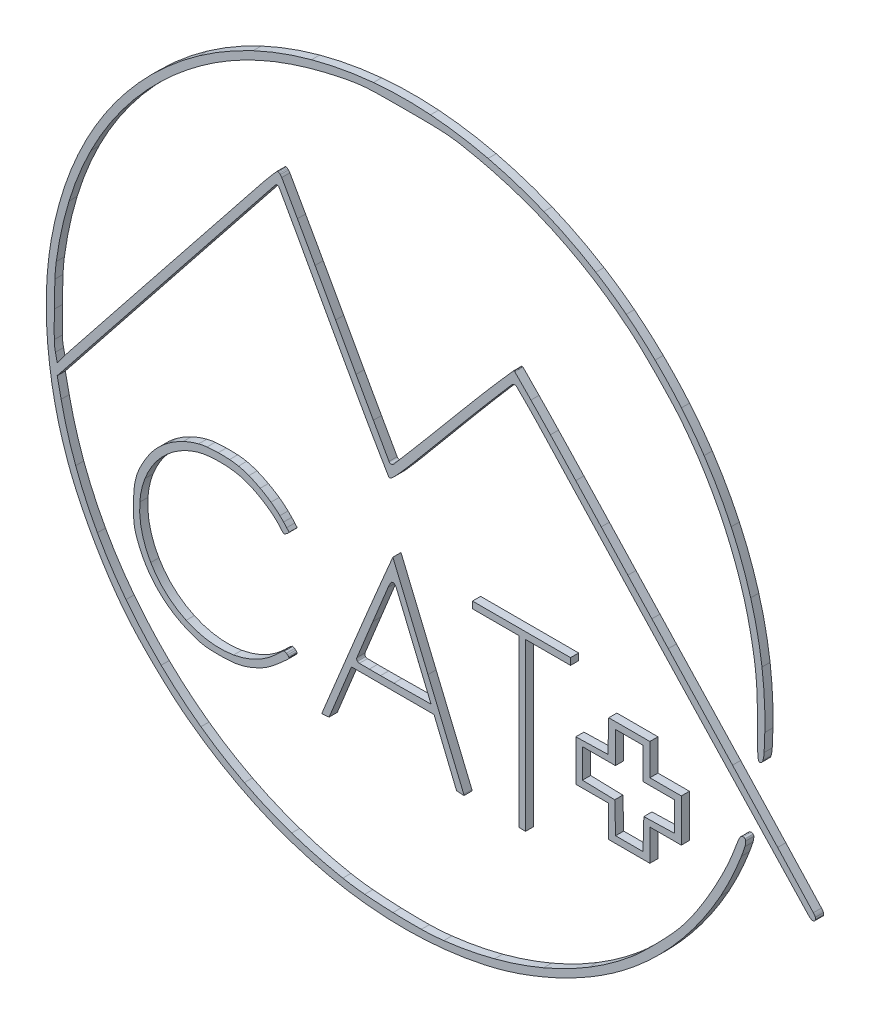
SolidWorks part; units mm, degrees
ref_plane "Front Plane" through (0, 0, 0) normal (0, 0, 1) x (1, 0, 0)
ref_plane "Top Plane" through (0, 0, 0) normal (0, 1, 0) x (1, 0, 0)
ref_plane "Right Plane" through (0, 0, 0) normal (1, 0, 0) x (0, 0, -1)
sketch "Sketch1" plane through (0, 0, 0) normal (0, 0, 1) x (1, 0, 0)
  line L0 (-31.8158, 8.4253) -> (-33.6826, 3.9005)
  line L1 (-33.6826, 3.9005) -> (-35.3286, -0.095)
  line L2 (-35.0091, -0.3817) -> (-34.2819, -0.3208)
  line L3 (-34.2819, -0.3208) -> (-32.5671, 3.8807)
  line L4 (-32.5671, 3.8807) -> (-30.7067, 8.4391)
  line L5 (-30.7067, 8.4391) -> (-24.0976, 8.4391)
  line L6 (-24.0976, 8.4391) -> (-17.4891, 8.4391)
  line L7 (-22.9021, 20.6991) -> (-23.6601, 22.512)
  line L8 (-22.019, 18.5844) -> (-22.9021, 20.6991)
  line L9 (-18.4139, 9.9357) -> (-21.0097, 16.164)
  line L10 (-23.9238, 9.8713) -> (-18.4139, 9.9357)
  line L11 (-29.4374, 9.8633) -> (-27.8429, 9.8536)
  line L12 (-27.0004, 16.312) -> (-29.5566, 10.0428)
  line L13 (-24.5684, 22.2594) -> (-27.0004, 16.312)
  line L14 (-22.9021, 20.6991) -> (-23.6601, 22.512) construction
  line L15 (-22.019, 18.5844) -> (-22.9021, 20.6991) construction
  line L16 (-18.4139, 9.9357) -> (-21.0097, 16.164) construction
  line L17 (-23.9238, 9.8713) -> (-18.4139, 9.9357) construction
  line L18 (-29.4374, 9.8633) -> (-27.8429, 9.8536) construction
  line L19 (-27.0004, 16.312) -> (-29.5566, 10.0428) construction
  line L20 (-24.5684, 22.2594) -> (-27.0004, 16.312) construction
  line L21 (-17.4891, 8.4391) -> (-15.6125, 3.8816)
  line L22 (-15.6125, 3.8816) -> (-13.8819, -0.3211)
  line L23 (-13.8819, -0.3211) -> (-13.1967, -0.3799)
  line L24 (-12.7232, -0.239) -> (-18.4542, 13.4865)
  line L25 (-18.4542, 13.4865) -> (-24.079, 26.9521)
  line L26 (-24.079, 26.9521) -> (-25.5848, 23.397)
  line L27 (-29.6297, 13.7137) -> (-31.8158, 8.4253)
  line L28 (-34.9841, -0.6807) -> (-34.0736, -0.6044)
  line L29 (-34.0736, -0.6044) -> (-32.2894, 3.7673)
  line L30 (-4.2103, 25.8657) -> (-4.2103, 12.5708)
  line L31 (-4.2103, 12.5708) -> (-4.2103, -0.7242)
  line L32 (-4.2103, -0.7242) -> (-3.3719, -0.7242)
  line L33 (-3.3719, -0.7242) -> (-2.5335, -0.7242)
  line L34 (-2.5335, -0.7242) -> (-2.5335, 12.5708)
  line L35 (-2.5335, 12.5708) -> (-2.5335, 25.8657)
  line L36 (-2.5335, 25.8657) -> (1.0598, 25.8657)
  line L37 (1.0598, 25.8657) -> (4.653, 25.8657)
  line L38 (4.653, 25.8657) -> (4.653, 26.7041)
  line L39 (4.653, 26.7041) -> (4.653, 27.5425)
  line L40 (4.653, 27.5425) -> (-3.4917, 27.5425)
  line L41 (-3.4917, 27.5425) -> (-11.6363, 27.5425)
  line L42 (-11.6363, 27.5425) -> (-11.6363, 26.7041)
  line L43 (-11.6363, 26.7041) -> (-11.6363, 25.8657)
  line L44 (-11.6363, 25.8657) -> (-7.9233, 25.8657)
  line L45 (-7.9233, 25.8657) -> (-4.2103, 25.8657)
  line L46 (-4.2103, 25.8657) -> (-4.2103, 12.5708) construction
  line L47 (-4.2103, 12.5708) -> (-4.2103, -0.7242) construction
  line L48 (-4.2103, -0.7242) -> (-3.3719, -0.7242) construction
  line L49 (-3.3719, -0.7242) -> (-2.5335, -0.7242) construction
  line L50 (-2.5335, -0.7242) -> (-2.5335, 12.5708) construction
  line L51 (-2.5335, 12.5708) -> (-2.5335, 25.8657) construction
  line L52 (-2.5335, 25.8657) -> (1.0598, 25.8657) construction
  line L53 (1.0598, 25.8657) -> (4.653, 25.8657) construction
  line L54 (4.653, 25.8657) -> (4.653, 26.7041) construction
  line L55 (4.653, 26.7041) -> (4.653, 27.5425) construction
  line L56 (4.653, 27.5425) -> (-3.4917, 27.5425) construction
  line L57 (-3.4917, 27.5425) -> (-11.6363, 27.5425) construction
  line L58 (-11.6363, 27.5425) -> (-11.6363, 26.7041) construction
  line L59 (-11.6363, 26.7041) -> (-11.6363, 25.8657) construction
  line L60 (-11.6363, 25.8657) -> (-7.9233, 25.8657) construction
  line L61 (-7.9233, 25.8657) -> (-4.2103, 25.8657) construction
  line L62 (-32.2894, 3.7673) -> (-30.5051, 8.1391)
  line L63 (-30.5051, 8.1391) -> (-24.0976, 8.1391)
  line L64 (-24.0976, 8.1391) -> (-17.69, 8.1391)
  line L65 (-17.69, 8.1391) -> (-15.8899, 3.7673)
  line L66 (-15.8899, 3.7673) -> (-14.0897, -0.6044)
  line L67 (-14.0897, -0.6044) -> (-13.2223, -0.6788)
  line L68 (-12.4463, -0.1234) -> (-18.1774, 13.6021)
  line L69 (-18.1774, 13.6021) -> (-23.962, 27.4502)
  line L70 (17.3491, 17.2419) -> (17.3491, 19.7572)
  line L71 (17.3491, 19.7572) -> (17.3491, 22.2725)
  line L72 (17.3491, 22.2725) -> (13.7639, 22.2725)
  line L73 (13.7639, 22.2725) -> (10.1788, 22.2725)
  line L74 (10.1788, 22.2725) -> (10.1108, 19.6973)
  line L75 (10.1108, 19.6973) -> (10.0428, 17.1222)
  line L76 (10.0428, 17.1222) -> (7.4677, 17.0542)
  line L77 (7.4677, 17.0542) -> (4.8925, 16.9862)
  line L78 (4.8925, 16.9862) -> (4.8925, 13.4011)
  line L79 (4.8925, 13.4011) -> (4.8925, 9.8159)
  line L80 (4.8925, 9.8159) -> (7.5276, 9.8159)
  line L81 (7.5276, 9.8159) -> (10.1626, 9.8159)
  line L82 (10.1626, 9.8159) -> (10.1626, 7.3007)
  line L83 (10.1626, 7.3007) -> (10.1626, 4.7854)
  line L84 (10.1626, 4.7854) -> (13.7558, 4.7854)
  line L85 (13.7558, 4.7854) -> (17.3491, 4.7854)
  line L86 (17.3491, 4.7854) -> (17.3491, 7.3007)
  line L87 (17.3491, 7.3007) -> (17.3491, 9.8159)
  line L88 (17.3491, 9.8159) -> (19.8643, 9.8159)
  line L89 (19.8643, 9.8159) -> (22.3796, 9.8159)
  line L90 (22.3796, 9.8159) -> (22.3796, 13.5289)
  line L91 (22.3796, 13.5289) -> (22.3796, 17.2419)
  line L92 (22.3796, 17.2419) -> (19.8643, 17.2419)
  line L93 (19.8643, 17.2419) -> (17.3491, 17.2419)
  line L94 (17.3491, 17.2419) -> (17.3491, 19.7572) construction
  line L95 (17.3491, 19.7572) -> (17.3491, 22.2725) construction
  line L96 (17.3491, 22.2725) -> (13.7639, 22.2725) construction
  line L97 (13.7639, 22.2725) -> (10.1788, 22.2725) construction
  line L98 (10.1788, 22.2725) -> (10.1108, 19.6973) construction
  line L99 (10.1108, 19.6973) -> (10.0428, 17.1222) construction
  line L100 (10.0428, 17.1222) -> (7.4677, 17.0542) construction
  line L101 (7.4677, 17.0542) -> (4.8925, 16.9862) construction
  line L102 (4.8925, 16.9862) -> (4.8925, 13.4011) construction
  line L103 (4.8925, 13.4011) -> (4.8925, 9.8159) construction
  line L104 (4.8925, 9.8159) -> (7.5276, 9.8159) construction
  line L105 (7.5276, 9.8159) -> (10.1626, 9.8159) construction
  line L106 (10.1626, 9.8159) -> (10.1626, 7.3007) construction
  line L107 (10.1626, 7.3007) -> (10.1626, 4.7854) construction
  line L108 (10.1626, 4.7854) -> (13.7558, 4.7854) construction
  line L109 (13.7558, 4.7854) -> (17.3491, 4.7854) construction
  line L110 (17.3491, 4.7854) -> (17.3491, 7.3007) construction
  line L111 (17.3491, 7.3007) -> (17.3491, 9.8159) construction
  line L112 (17.3491, 9.8159) -> (19.8643, 9.8159) construction
  line L113 (19.8643, 9.8159) -> (22.3796, 9.8159) construction
  line L114 (22.3796, 9.8159) -> (22.3796, 13.5289) construction
  line L115 (22.3796, 13.5289) -> (22.3796, 17.2419) construction
  line L116 (22.3796, 17.2419) -> (19.8643, 17.2419) construction
  line L117 (19.8643, 17.2419) -> (17.3491, 17.2419) construction
  line L118 (11.7879, 8.9176) -> (11.8562, 6.4623)
  line L119 (11.7197, 11.373) -> (11.7879, 8.9176)
  line L120 (9.1445, 11.441) -> (11.7197, 11.373)
  line L121 (6.5694, 11.509) -> (9.1445, 11.441)
  line L122 (6.5694, 13.5371) -> (6.5694, 11.509)
  line L123 (6.5694, 15.5651) -> (6.5694, 13.5371)
  line L124 (9.2044, 15.5651) -> (6.5694, 15.5651)
  line L125 (11.8394, 15.5651) -> (9.2044, 15.5651)
  line L126 (11.8394, 18.0804) -> (11.8394, 15.5651)
  line L127 (11.8394, 20.5956) -> (11.8394, 18.0804)
  line L128 (13.7558, 20.5956) -> (11.8394, 20.5956)
  line L129 (15.6722, 20.5956) -> (13.7558, 20.5956)
  line L130 (15.6722, 18.0804) -> (15.6722, 20.5956)
  line L131 (15.6722, 15.5651) -> (15.6722, 18.0804)
  line L132 (18.1875, 15.5651) -> (15.6722, 15.5651)
  line L133 (20.7027, 15.5651) -> (18.1875, 15.5651)
  line L134 (20.7027, 13.5373) -> (20.7027, 15.5651)
  line L135 (20.7027, 11.5095) -> (20.7027, 13.5373)
  line L136 (18.2474, 11.4413) -> (20.7027, 11.5095)
  line L137 (15.792, 11.373) -> (18.2474, 11.4413)
  line L138 (15.7237, 8.9176) -> (15.792, 11.373)
  line L139 (15.6555, 6.4623) -> (15.7237, 8.9176)
  line L140 (13.7558, 6.4623) -> (15.6555, 6.4623)
  line L141 (11.8562, 6.4623) -> (13.7558, 6.4623)
  line L142 (11.7879, 8.9176) -> (11.8562, 6.4623) construction
  line L143 (11.7197, 11.373) -> (11.7879, 8.9176) construction
  line L144 (9.1445, 11.441) -> (11.7197, 11.373) construction
  line L145 (6.5694, 11.509) -> (9.1445, 11.441) construction
  line L146 (6.5694, 13.5371) -> (6.5694, 11.509) construction
  line L147 (6.5694, 15.5651) -> (6.5694, 13.5371) construction
  line L148 (9.2044, 15.5651) -> (6.5694, 15.5651) construction
  line L149 (11.8394, 15.5651) -> (9.2044, 15.5651) construction
  line L150 (11.8394, 18.0804) -> (11.8394, 15.5651) construction
  line L151 (11.8394, 20.5956) -> (11.8394, 18.0804) construction
  line L152 (13.7558, 20.5956) -> (11.8394, 20.5956) construction
  line L153 (15.6722, 20.5956) -> (13.7558, 20.5956) construction
  line L154 (15.6722, 18.0804) -> (15.6722, 20.5956) construction
  line L155 (15.6722, 15.5651) -> (15.6722, 18.0804) construction
  line L156 (18.1875, 15.5651) -> (15.6722, 15.5651) construction
  line L157 (20.7027, 15.5651) -> (18.1875, 15.5651) construction
  line L158 (20.7027, 13.5373) -> (20.7027, 15.5651) construction
  line L159 (20.7027, 11.5095) -> (20.7027, 13.5373) construction
  line L160 (18.2474, 11.4413) -> (20.7027, 11.5095) construction
  line L161 (15.792, 11.373) -> (18.2474, 11.4413) construction
  line L162 (15.7237, 8.9176) -> (15.792, 11.373) construction
  line L163 (15.6555, 6.4623) -> (15.7237, 8.9176) construction
  line L164 (13.7558, 6.4623) -> (15.6555, 6.4623) construction
  line L165 (11.8562, 6.4623) -> (13.7558, 6.4623) construction
  line L166 (-24.1758, 27.4927) -> (-25.861, 23.514)
  line L167 (-29.9069, 13.8284) -> (-32.0931, 8.5398)
  line L168 (-32.0931, 8.5398) -> (-33.9599, 4.0148)
  line L169 (-33.9599, 4.0148) -> (-35.606, 0.0193)
  line L170 (-34.9841, -0.6807) -> (-34.0736, -0.6044) construction
  line L171 (-34.0736, -0.6044) -> (-32.2894, 3.7673) construction
  line L172 (-32.2894, 3.7673) -> (-30.5051, 8.1391) construction
  line L173 (-30.5051, 8.1391) -> (-24.0976, 8.1391) construction
  line L174 (-24.0976, 8.1391) -> (-17.69, 8.1391) construction
  line L175 (-17.69, 8.1391) -> (-15.8899, 3.7673) construction
  line L176 (-15.8899, 3.7673) -> (-14.0897, -0.6044) construction
  line L177 (-14.0897, -0.6044) -> (-13.2223, -0.6788) construction
  line L178 (-12.4463, -0.1234) -> (-18.1774, 13.6021) construction
  line L179 (-18.1774, 13.6021) -> (-23.962, 27.4502) construction
  line L180 (-24.1758, 27.4927) -> (-25.861, 23.514) construction
  line L181 (-29.9069, 13.8284) -> (-32.0931, 8.5398) construction
  line L182 (-32.0931, 8.5398) -> (-33.9599, 4.0148) construction
  line L183 (-33.9599, 4.0148) -> (-35.606, 0.0193) construction
  line L184 (-3.9103, 26.1657) -> (-3.9103, 12.5708)
  line L185 (-3.9103, 12.5708) -> (-3.9103, -0.4242)
  line L186 (-3.9103, -0.4242) -> (-3.3719, -0.4242)
  line L187 (-3.3719, -0.4242) -> (-2.8335, -0.4242)
  line L188 (-2.8335, -0.4242) -> (-2.8335, 12.5708)
  line L189 (-2.8335, 12.5708) -> (-2.8335, 26.1657)
  line L190 (-2.8335, 26.1657) -> (1.0598, 26.1657)
  line L191 (1.0598, 26.1657) -> (4.353, 26.1657)
  line L192 (4.353, 26.1657) -> (4.353, 26.7041)
  line L193 (4.353, 26.7041) -> (4.353, 27.2425)
  line L194 (4.353, 27.2425) -> (-3.4917, 27.2425)
  line L195 (-3.4917, 27.2425) -> (-11.3363, 27.2425)
  line L196 (-11.3363, 27.2425) -> (-11.3363, 26.7041)
  line L197 (-11.3363, 26.7041) -> (-11.3363, 26.1657)
  line L198 (-11.3363, 26.1657) -> (-7.9233, 26.1657)
  line L199 (-67.8439, 40.1395) -> (-72.5046, 34.276)
  line L200 (-72.5046, 34.276) -> (-76.5741, 29.1498)
  line L201 (-77.0417, 28.5385) -> (-77.6319, 27.7379)
  line L202 (-77.6319, 27.7379) -> (-77.7832, 28.4188)
  line L203 (-76.8703, 22.3465) -> (-77.4657, 25.1753)
  line L204 (-77.4657, 25.1753) -> (-60.088, 47.02)
  line L205 (-60.088, 47.02) -> (-53.4199, 55.4018)
  line L206 (-53.4199, 55.4018) -> (-47.7953, 62.4715)
  line L207 (-47.7953, 62.4715) -> (-42.6976, 68.8786)
  line L208 (-42.6976, 68.8786) -> (-42.6433, 68.9453)
  line L209 (-42.5371, 68.9359) -> (-41.5992, 67.2705)
  line L210 (-39.9192, 64.2509) -> (-33.3383, 52.3358)
  line L211 (-20.6106, 41.4431) -> (-13.8056, 49.581)
  line L212 (-7.4365, 57.1218) -> (-4.8104, 60.1774)
  line L213 (28.4615, 25.0635) -> (42.2651, 10.3208)
  line L214 (43.434, 11.5266) -> (37.7243, 17.7163)
  line L215 (30.4978, 25.5079) -> (20.2201, 36.5214)
  line L216 (20.2201, 36.5214) -> (17.5906, 39.3369)
  line L217 (17.5906, 39.3369) -> (13.7451, 43.4589)
  line L218 (13.7451, 43.4589) -> (9.4879, 48.0248)
  line L219 (9.4879, 48.0248) -> (5.4148, 52.3957)
  line L220 (-21.4082, 43.3415) -> (-24.2103, 40.0511)
  line L221 (-24.4251, 40.0588) -> (-26.9342, 44.5176)
  line L222 (-39.0894, 66.369) -> (-41.5971, 70.8175)
  line L223 (-45.705, 67.9417) -> (-47.4272, 65.7766)
  line L224 (-47.4272, 65.7766) -> (-51.7273, 60.3763)
  line L225 (-51.7273, 60.3763) -> (-56.8563, 53.9363)
  line L226 (-56.8563, 53.9363) -> (-62.4248, 46.946)
  line L227 (-62.4248, 46.946) -> (-67.8439, 40.1395)
  line L228 (-67.8439, 40.1395) -> (-72.5046, 34.276) construction
  line L229 (-72.5046, 34.276) -> (-76.5741, 29.1498) construction
  line L230 (-77.0417, 28.5385) -> (-77.6319, 27.7379) construction
  line L231 (-77.6319, 27.7379) -> (-77.7832, 28.4188) construction
  line L232 (-76.8703, 22.3465) -> (-77.4657, 25.1753) construction
  line L233 (-77.4657, 25.1753) -> (-60.088, 47.02) construction
  line L234 (-60.088, 47.02) -> (-53.4199, 55.4018) construction
  line L235 (-53.4199, 55.4018) -> (-47.7953, 62.4715) construction
  line L236 (-47.7953, 62.4715) -> (-42.6976, 68.8786) construction
  line L237 (-42.6976, 68.8786) -> (-42.6433, 68.9453) construction
  line L238 (-42.5371, 68.9359) -> (-41.5992, 67.2705) construction
  line L239 (-39.9192, 64.2509) -> (-33.3383, 52.3358) construction
  line L240 (-20.6106, 41.4431) -> (-13.8056, 49.581) construction
  line L241 (-7.4365, 57.1218) -> (-4.8104, 60.1774) construction
  line L242 (28.4615, 25.0635) -> (42.2651, 10.3208) construction
  line L243 (43.434, 11.5266) -> (37.7243, 17.7163) construction
  line L244 (30.4978, 25.5079) -> (20.2201, 36.5214) construction
  line L245 (20.2201, 36.5214) -> (17.5906, 39.3369) construction
  line L246 (17.5906, 39.3369) -> (13.7451, 43.4589) construction
  line L247 (13.7451, 43.4589) -> (9.4879, 48.0248) construction
  line L248 (9.4879, 48.0248) -> (5.4148, 52.3957) construction
  line L249 (-21.4082, 43.3415) -> (-24.2103, 40.0511) construction
  line L250 (-24.4251, 40.0588) -> (-26.9342, 44.5176) construction
  line L251 (-39.0894, 66.369) -> (-41.5971, 70.8175) construction
  line L252 (-45.705, 67.9417) -> (-47.4272, 65.7766) construction
  line L253 (-47.4272, 65.7766) -> (-51.7273, 60.3763) construction
  line L254 (-51.7273, 60.3763) -> (-56.8563, 53.9363) construction
  line L255 (-56.8563, 53.9363) -> (-62.4248, 46.946) construction
  line L256 (-62.4248, 46.946) -> (-67.8439, 40.1395) construction
  line L257 (-7.9233, 26.1657) -> (-3.9103, 26.1657)
  line L258 (7.4756, 16.7543) -> (5.1925, 16.694)
  line L259 (5.1925, 16.694) -> (5.1925, 13.4011)
  line L260 (5.1925, 13.4011) -> (5.1925, 10.1159)
  line L261 (5.1925, 10.1159) -> (7.5276, 10.1159)
  line L262 (7.5276, 10.1159) -> (10.4626, 10.1159)
  line L263 (10.4626, 10.1159) -> (10.4626, 7.3007)
  line L264 (10.4626, 7.3007) -> (10.4626, 5.0854)
  line L265 (10.4626, 5.0854) -> (13.7558, 5.0854)
  line L266 (13.7558, 5.0854) -> (17.0491, 5.0854)
  line L267 (17.0491, 5.0854) -> (17.0491, 7.3007)
  line L268 (17.0491, 7.3007) -> (17.0491, 10.1159)
  line L269 (17.0491, 10.1159) -> (19.8643, 10.1159)
  line L270 (19.8643, 10.1159) -> (22.0796, 10.1159)
  line L271 (22.0796, 10.1159) -> (22.0796, 13.5289)
  line L272 (22.0796, 13.5289) -> (22.0796, 16.9419)
  line L273 (22.0796, 16.9419) -> (19.8643, 16.9419)
  line L274 (19.8643, 16.9419) -> (17.0491, 16.9419)
  line L275 (17.0491, 16.9419) -> (17.0491, 19.7572)
  line L276 (17.0491, 19.7572) -> (17.0491, 21.9725)
  line L277 (17.0491, 21.9725) -> (13.7639, 21.9725)
  line L278 (13.7639, 21.9725) -> (10.471, 21.9725)
  line L279 (10.471, 21.9725) -> (10.4107, 19.6894)
  line L280 (10.4107, 19.6894) -> (10.3352, 16.8298)
  line L281 (10.3352, 16.8298) -> (7.4756, 16.7543)
  line L282 (28.6805, 25.2685) -> (42.4841, 10.5258)
  line L283 (43.2134, 11.3232) -> (37.5039, 17.5129)
  line L284 (30.2783, 25.3034) -> (20.0008, 36.3167)
  line L285 (20.0008, 36.3167) -> (17.3713, 39.1322)
  line L286 (17.3713, 39.1322) -> (13.5257, 43.2543)
  line L287 (13.5257, 43.2543) -> (9.2684, 47.8202)
  line L288 (9.2684, 47.8202) -> (5.1953, 52.1912)
  line L289 (-21.1798, 43.147) -> (-23.9819, 39.8566)
  line L290 (-24.6865, 39.9116) -> (-27.1956, 44.3705)
  line L291 (-39.3507, 66.2217) -> (-41.8584, 70.6701)
  line L292 (-45.4701, 67.755) -> (-47.1925, 65.5898)
  line L293 (-47.1925, 65.5898) -> (-51.4927, 60.1894)
  line L294 (-51.4927, 60.1894) -> (-56.6217, 53.7494)
  line L295 (-56.6217, 53.7494) -> (-62.1902, 46.7591)
  line L296 (-62.1902, 46.7591) -> (-67.6091, 39.9527)
  line L297 (-67.6091, 39.9527) -> (-72.2697, 34.0894)
  line L298 (-72.2697, 34.0894) -> (-76.3391, 28.9633)
  line L299 (-76.8003, 28.3605) -> (-77.7817, 27.0292)
  line L300 (-77.7817, 27.0292) -> (-78.0761, 28.3537)
  line L301 (-77.1639, 22.2847) -> (-77.7883, 25.2516)
  line L302 (-77.7883, 25.2516) -> (-60.3228, 47.2067)
  line L303 (-60.3228, 47.2067) -> (-53.6547, 55.5886)
  line L304 (-53.6547, 55.5886) -> (-48.0301, 62.6583)
  line L305 (-48.0301, 62.6583) -> (-42.9314, 69.0666)
  line L306 (-42.9314, 69.0666) -> (-42.8751, 69.1358)
  line L307 (-42.2759, 69.0834) -> (-41.3376, 67.4174)
  line L308 (-39.6566, 64.3959) -> (-33.0757, 52.4808)
  line L309 (-20.8407, 41.6357) -> (-14.0359, 49.7733)
  line L310 (-7.6641, 57.3173) -> (-5.0379, 60.373)
  line L311 (-23.9203, 9.5714) -> (-17.966, 9.6409)
  line L312 (-17.966, 9.6409) -> (-20.7328, 16.2794)
  line L313 (-21.7421, 18.6999) -> (-22.6253, 20.8148)
  line L314 (-22.6253, 20.8148) -> (-23.3833, 22.6277)
  line L315 (-24.846, 22.373) -> (-27.2781, 16.4254)
  line L316 (-27.2781, 16.4254) -> (-29.8344, 10.156)
  line L317 (-29.4393, 9.5633) -> (-27.8446, 9.5536)
  line L318 (9.2044, 15.8651) -> (6.2694, 15.8651)
  line L319 (6.2694, 15.8651) -> (6.2694, 13.5371)
  line L320 (6.2694, 13.5371) -> (6.2694, 11.2168)
  line L321 (6.2694, 11.2168) -> (9.1366, 11.1411)
  line L322 (9.1366, 11.1411) -> (11.4277, 11.0806)
  line L323 (11.4277, 11.0806) -> (11.488, 8.9093)
  line L324 (11.488, 8.9093) -> (11.5644, 6.1623)
  line L325 (11.5644, 6.1623) -> (13.7558, 6.1623)
  line L326 (13.7558, 6.1623) -> (15.9472, 6.1623)
  line L327 (15.9472, 6.1623) -> (16.0236, 8.9093)
  line L328 (16.0236, 8.9093) -> (16.084, 11.081)
  line L329 (16.084, 11.081) -> (18.2557, 11.1414)
  line L330 (18.2557, 11.1414) -> (21.0027, 11.2178)
  line L331 (21.0027, 11.2178) -> (21.0027, 13.5373)
  line L332 (21.0027, 13.5373) -> (21.0027, 15.8651)
  line L333 (21.0027, 15.8651) -> (18.1875, 15.8651)
  line L334 (18.1875, 15.8651) -> (15.9722, 15.8651)
  line L335 (15.9722, 15.8651) -> (15.9722, 18.0804)
  line L336 (15.9722, 18.0804) -> (15.9722, 20.8956)
  line L337 (15.9722, 20.8956) -> (13.7558, 20.8956)
  line L338 (13.7558, 20.8956) -> (11.5394, 20.8956)
  line L339 (11.5394, 20.8956) -> (11.5394, 18.0804)
  line L340 (11.5394, 18.0804) -> (11.5394, 15.8651)
  line L341 (11.5394, 15.8651) -> (9.2044, 15.8651)
  arc A0 (-49.5642, 0.6571) -> (-42.7219, 4.1582) centre (-51.7823, 13.4286) ccw
  arc A1 (-41.8156, 5.0244) -> (-42.7219, 4.1582) centre (-3.3331, -36.1437) ccw
  arc A2 (-41.4955, 5.2491) -> (-41.8156, 5.0244) centre (-40.857, 3.9989) ccw
  arc A3 (-41.3987, 5.26) -> (-41.4955, 5.2491) centre (-41.4327, 5.1263) ccw
  arc A4 (-41.1133, 5.1343) -> (-41.3987, 5.26) centre (-41.6323, 4.3423) ccw
  arc A5 (-40.922, 4.994) -> (-41.1133, 5.1343) centre (-42.3375, 3.266) ccw
  arc A6 (-40.7674, 4.8494) -> (-40.922, 4.994) centre (-41.9471, 3.7426) ccw
  arc A7 (-40.6833, 4.7493) -> (-40.7674, 4.8494) centre (-41.637, 4.0335) ccw
  arc A8 (-40.6833, 4.7493) -> (-40.6833, 4.7493) centre (-40.6833, 4.7493) ccw
  arc A9 (-40.8183, 4.4664) -> (-40.6833, 4.7493) centre (-41.1142, 4.7812) ccw
  arc A10 (-42.2689, 3.157) -> (-40.8183, 4.4664) centre (-73.8574, 39.6118) ccw
  arc A11 (-21.0097, 16.164) -> (-22.019, 18.5844) centre (-6012.5595, -2480.9412) ccw
  arc A12 (-26.0431, 9.8534) -> (-23.9238, 9.8713) centre (-27.7435, 336.7015) ccw
  arc A13 (-27.8429, 9.8536) -> (-26.0431, 9.8534) centre (-26.9317, 180.6158) ccw
  arc A14 (-29.528, 9.9012) -> (-29.4374, 9.8633) centre (-29.4365, 9.9928) ccw
  arc A15 (-29.5566, 10.0428) -> (-29.528, 9.9012) centre (-29.4358, 9.9935) ccw
  arc A16 (-24.1455, 23.0963) -> (-24.5684, 22.2594) centre (-19.0595, 20.0012) ccw
  arc A17 (-24.0763, 23.1408) -> (-24.1455, 23.0963) centre (-24.0652, 23.0475) ccw
  arc A18 (-23.9896, 23.1188) -> (-24.0763, 23.1408) centre (-24.0616, 23.017) ccw
  arc A19 (-23.894, 23.0192) -> (-23.9896, 23.1188) centre (-24.2004, 22.8209) ccw
  arc A20 (-23.807, 22.8568) -> (-23.894, 23.0192) centre (-24.8316, 22.4122) ccw
  arc A21 (-23.6601, 22.512) -> (-23.807, 22.8568) centre (-49.7846, 11.5854) ccw
  arc A22 (-21.0097, 16.164) -> (-22.019, 18.5844) centre (-6012.5595, -2480.9412) ccw construction
  arc A23 (-26.0431, 9.8534) -> (-23.9238, 9.8713) centre (-27.7435, 336.7015) ccw construction
  arc A24 (-27.8429, 9.8536) -> (-26.0431, 9.8534) centre (-26.9317, 180.6158) ccw construction
  arc A25 (-29.528, 9.9012) -> (-29.4374, 9.8633) centre (-29.4365, 9.9928) ccw construction
  arc A26 (-29.5566, 10.0428) -> (-29.528, 9.9012) centre (-29.4358, 9.9935) ccw construction
  arc A27 (-24.1455, 23.0963) -> (-24.5684, 22.2594) centre (-19.0595, 20.0012) ccw construction
  arc A28 (-24.0763, 23.1408) -> (-24.1455, 23.0963) centre (-24.0652, 23.0475) ccw construction
  arc A29 (-23.9896, 23.1188) -> (-24.0763, 23.1408) centre (-24.0616, 23.017) ccw construction
  arc A30 (-23.894, 23.0192) -> (-23.9896, 23.1188) centre (-24.2004, 22.8209) ccw construction
  arc A31 (-23.807, 22.8568) -> (-23.894, 23.0192) centre (-24.8316, 22.4122) ccw construction
  arc A32 (-23.6601, 22.512) -> (-23.807, 22.8568) centre (-49.7846, 11.5854) ccw construction
  arc A33 (-43.81, 1.9118) -> (-42.2689, 3.157) centre (-61.1247, 24.9176) ccw
  arc A34 (-45.0281, 1.1418) -> (-43.81, 1.9118) centre (-49.137, 8.9897) ccw
  arc A35 (-46.7842, 0.3231) -> (-45.0281, 1.1418) centre (-54.7837, 19.7748) ccw
  arc A36 (-13.2223, -0.6788) -> (-12.8898, -0.6948) centre (-12.8426, 3.7515) ccw
  arc A37 (-12.8898, -0.6948) -> (-12.6098, -0.6803) centre (-12.8659, 1.5583) ccw
  arc A38 (-12.6098, -0.6803) -> (-12.4044, -0.6429) centre (-12.7893, 0.8886) ccw
  arc A39 (-12.4044, -0.6429) -> (-12.355, -0.5795) centre (-12.4203, -0.5795) ccw
  arc A40 (-12.355, -0.5795) -> (-12.4463, -0.1234) centre (-13.5391, -0.5795) ccw
  arc A41 (-23.962, 27.4502) -> (-24.1006, 27.5425) centre (-24.1006, 27.3923) ccw
  arc A42 (-24.1006, 27.5425) -> (-24.1758, 27.4927) centre (-24.1006, 27.4608) ccw
  arc A43 (-25.861, 23.514) -> (-27.7219, 19.0869) centre (833.8396, -340.4685) ccw
  arc A44 (-27.7219, 19.0869) -> (-29.9069, 13.8284) centre (1667.4833, -688.3721) ccw
  arc A45 (-35.606, 0.0193) -> (-35.7375, -0.3213) centre (-28.0357, -3.0987) ccw
  arc A46 (-35.7375, -0.3213) -> (-35.7814, -0.55) centre (-35.0335, -0.5752) ccw
  arc A47 (-35.7814, -0.55) -> (-35.7096, -0.6682) centre (-35.6552, -0.5543) ccw
  arc A48 (-35.7096, -0.6682) -> (-35.5006, -0.7116) centre (-35.5167, -0.2639) ccw
  arc A49 (-35.5006, -0.7116) -> (-34.9841, -0.6807) centre (-35.8917, 10.1573) ccw
  arc A50 (-13.2223, -0.6788) -> (-12.8898, -0.6948) centre (-12.8426, 3.7515) ccw construction
  arc A51 (-12.8898, -0.6948) -> (-12.6098, -0.6803) centre (-12.8659, 1.5583) ccw construction
  arc A52 (-12.6098, -0.6803) -> (-12.4044, -0.6429) centre (-12.7893, 0.8886) ccw construction
  arc A53 (-12.4044, -0.6429) -> (-12.355, -0.5795) centre (-12.4203, -0.5795) ccw construction
  arc A54 (-12.355, -0.5795) -> (-12.4463, -0.1234) centre (-13.5391, -0.5795) ccw construction
  arc A55 (-23.962, 27.4502) -> (-24.1006, 27.5425) centre (-24.1006, 27.3923) ccw construction
  arc A56 (-24.1006, 27.5425) -> (-24.1758, 27.4927) centre (-24.1006, 27.4608) ccw construction
  arc A57 (-25.861, 23.514) -> (-27.7219, 19.0869) centre (833.8396, -340.4685) ccw construction
  arc A58 (-27.7219, 19.0869) -> (-29.9069, 13.8284) centre (1667.4833, -688.3721) ccw construction
  arc A59 (-35.606, 0.0193) -> (-35.7375, -0.3213) centre (-28.0357, -3.0987) ccw construction
  arc A60 (-35.7375, -0.3213) -> (-35.7814, -0.55) centre (-35.0335, -0.5752) ccw construction
  arc A61 (-35.7814, -0.55) -> (-35.7096, -0.6682) centre (-35.6552, -0.5543) ccw construction
  arc A62 (-35.7096, -0.6682) -> (-35.5006, -0.7116) centre (-35.5167, -0.2639) ccw construction
  arc A63 (-35.5006, -0.7116) -> (-34.9841, -0.6807) centre (-35.8917, 10.1573) ccw construction
  arc A64 (-48.3161, -0.1739) -> (-46.7842, 0.3231) centre (-50.7942, 10.0738) ccw
  arc A65 (-49.9147, -0.4342) -> (-48.3161, -0.1739) centre (-50.8271, 10.2102) ccw
  arc A66 (-51.8794, -0.5146) -> (-49.9147, -0.4342) centre (-51.7992, 21.5509) ccw
  arc A67 (-53.2559, -0.4829) -> (-51.8794, -0.5146) centre (-51.7507, 34.9203) ccw
  arc A68 (-54.2082, -0.3925) -> (-53.2559, -0.4829) centre (-52.8662, 8.6834) ccw
  arc A69 (-55.051, -0.2149) -> (-54.2082, -0.3925) centre (-53.1722, 6.6139) ccw
  arc A70 (-56.0525, 0.0998) -> (-55.051, -0.2149) centre (-51.185, 13.8367) ccw
  arc A71 (-59.083, 1.5543) -> (-56.0525, 0.0998) centre (-50.7934, 14.9419) ccw
  arc A72 (-61.6292, 3.5777) -> (-59.083, 1.5543) centre (-51.7536, 13.3912) ccw
  arc A73 (-63.6338, 6.1339) -> (-61.6292, 3.5777) centre (-51.778, 13.367) ccw
  arc A74 (-65.0612, 9.1652) -> (-63.6338, 6.1339) centre (-50.3288, 14.2512) ccw
  arc A75 (-65.3353, 10.0913) -> (-65.0612, 9.1652) centre (-54.8469, 12.6914) ccw
  arc A76 (-65.49, 10.9333) -> (-65.3353, 10.0913) centre (-58.5506, 11.7732) ccw
  arc A77 (-65.5658, 11.9603) -> (-65.49, 10.9333) centre (-54.5518, 12.2572) ccw
  arc A78 (-65.5848, 13.5281) -> (-65.5658, 11.9603) centre (-12.7952, 13.3831) ccw
  arc A79 (-65.4757, 15.7956) -> (-65.5848, 13.5281) centre (-40.5503, 13.4594) ccw
  arc A80 (-65.1534, 17.5257) -> (-65.4757, 15.7956) centre (-55.8054, 14.8892) ccw
  arc A81 (-64.5283, 19.1522) -> (-65.1534, 17.5257) centre (-56.0276, 14.9519) ccw
  arc A82 (-63.4535, 21.0873) -> (-64.5283, 19.1522) centre (-43.8628, 8.941) ccw
  arc A83 (-61.8965, 23.1114) -> (-63.4535, 21.0873) centre (-52.6608, 14.3958) ccw
  arc A84 (-59.9216, 24.8485) -> (-61.8965, 23.1114) centre (-51.5905, 13.3858) ccw
  arc A85 (-57.6362, 26.2077) -> (-59.9216, 24.8485) centre (-51.4079, 13.1345) ccw
  arc A86 (-55.1579, 27.1144) -> (-57.6362, 26.2077) centre (-51.5829, 13.502) ccw
  arc A87 (-53.8176, 27.3526) -> (-55.1579, 27.1144) centre (-53.0199, 18.9736) ccw
  arc A88 (-52.0273, 27.4536) -> (-53.8176, 27.3526) centre (-51.6115, 4.1786) ccw
  arc A89 (-50.2122, 27.4161) -> (-52.0273, 27.4536) centre (-51.6066, 3.9053) ccw
  arc A90 (-48.7787, 27.2271) -> (-50.2122, 27.4161) centre (-50.8087, 17.3587) ccw
  arc A91 (-47.119, 26.7328) -> (-48.7787, 27.2271) centre (-50.7959, 17.4207) ccw
  arc A92 (-45.3048, 25.8906) -> (-47.119, 26.7328) centre (-53.3959, 10.8362) ccw
  arc A93 (-43.5744, 24.827) -> (-45.3048, 25.8906) centre (-53.6028, 10.4514) ccw
  arc A94 (-50.1945, 27.7155) -> (-52.0327, 27.7536) centre (-51.6066, 3.9053) ccw
  arc A95 (-52.0327, 27.7536) -> (-53.846, 27.6512) centre (-51.6115, 4.1786) ccw
  arc A96 (-53.846, 27.6512) -> (-55.2341, 27.4045) centre (-53.0199, 18.9736) ccw
  arc A97 (-55.2341, 27.4045) -> (-57.7652, 26.4786) centre (-51.5829, 13.502) ccw
  arc A98 (-57.7652, 26.4786) -> (-60.098, 25.0912) centre (-51.4079, 13.1345) ccw
  arc A99 (-60.098, 25.0912) -> (-62.1146, 23.3173) centre (-51.5905, 13.3858) ccw
  arc A100 (-62.1146, 23.3173) -> (-63.7085, 21.2454) centre (-52.6608, 14.3958) ccw
  arc A101 (-63.7085, 21.2454) -> (-64.7972, 19.2851) centre (-43.8628, 8.941) ccw
  arc A102 (-64.7972, 19.2851) -> (-65.4421, 17.6071) centre (-56.0276, 14.9519) ccw
  arc A103 (-65.4421, 17.6071) -> (-65.7743, 15.8236) centre (-55.8054, 14.8892) ccw
  arc A104 (-65.7743, 15.8236) -> (-65.8848, 13.5289) centre (-40.5503, 13.4594) ccw
  arc A105 (-65.8848, 13.5289) -> (-65.8657, 11.9522) centre (-12.7952, 13.3831) ccw
  arc A106 (-65.8657, 11.9522) -> (-65.7878, 10.8973) centre (-54.5518, 12.2572) ccw
  arc A107 (-65.7878, 10.8973) -> (-65.6265, 10.0191) centre (-58.5506, 11.7732) ccw
  arc A108 (-65.6265, 10.0191) -> (-65.3448, 9.0673) centre (-54.8469, 12.6914) ccw
  arc A109 (-65.3448, 9.0673) -> (-63.8899, 5.9777) centre (-50.3288, 14.2512) ccw
  arc A110 (-63.8899, 5.9777) -> (-61.842, 3.3662) centre (-51.778, 13.367) ccw
  arc A111 (-61.842, 3.3662) -> (-59.2409, 1.2992) centre (-51.7536, 13.3912) ccw
  arc A112 (-59.2409, 1.2992) -> (-56.1527, -0.1829) centre (-50.7934, 14.9419) ccw
  arc A113 (-56.1527, -0.1829) -> (-55.1306, -0.5042) centre (-51.185, 13.8367) ccw
  arc A114 (-55.1306, -0.5042) -> (-54.252, -0.6893) centre (-53.1722, 6.6139) ccw
  arc A115 (-54.252, -0.6893) -> (-53.2686, -0.7826) centre (-52.8662, 8.6834) ccw
  arc A116 (-53.2686, -0.7826) -> (-51.8805, -0.8146) centre (-51.7507, 34.9203) ccw
  arc A117 (-51.8805, -0.8146) -> (-49.8891, -0.7331) centre (-51.7992, 21.5509) ccw
  arc A118 (-49.8891, -0.7331) -> (-48.2456, -0.4655) centre (-50.8271, 10.2102) ccw
  arc A119 (-48.2456, -0.4655) -> (-46.6701, 0.0456) centre (-50.7942, 10.0738) ccw
  arc A120 (-46.6701, 0.0456) -> (-44.889, 0.876) centre (-54.7837, 19.7748) ccw
  arc A121 (-44.889, 0.876) -> (-43.6296, 1.6721) centre (-49.137, 8.9897) ccw
  arc A122 (-43.6296, 1.6721) -> (-42.0724, 2.9303) centre (-61.1247, 24.9176) ccw
  arc A123 (-42.0724, 2.9303) -> (-40.6128, 4.2478) centre (-73.8574, 39.6118) ccw
  arc A124 (-40.6128, 4.2478) -> (-40.3821, 4.7812) centre (-41.1142, 4.7812) ccw
  arc A125 (-40.3821, 4.7812) -> (-40.4182, 4.8949) centre (-40.5791, 4.7812) ccw
  arc A126 (-40.4182, 4.8949) -> (-40.5486, 5.0547) centre (-41.637, 4.0335) ccw
  arc A127 (-40.5486, 5.0547) -> (-40.7319, 5.226) centre (-41.9471, 3.7426) ccw
  arc A128 (-40.7319, 5.226) -> (-40.9489, 5.3853) centre (-42.3375, 3.266) ccw
  arc A129 (-40.9489, 5.3853) -> (-41.3247, 5.5507) centre (-41.6323, 4.3423) ccw
  arc A130 (-41.3247, 5.5507) -> (-41.6319, 5.5163) centre (-41.4327, 5.1263) ccw
  arc A131 (-41.6319, 5.5163) -> (-42.0205, 5.2436) centre (-40.857, 3.9989) ccw
  arc A132 (-42.0205, 5.2436) -> (-42.9316, 4.3727) centre (-3.3331, -36.1437) ccw
  arc A133 (-49.6156, 0.9526) -> (-42.9316, 4.3727) centre (-51.7823, 13.4286) ccw
  arc A134 (-57.0308, 1.9378) -> (-49.6156, 0.9526) centre (-51.7533, 13.2616) ccw
  arc A135 (-62.5666, 6.9867) -> (-57.0308, 1.9378) centre (-51.7325, 13.3064) ccw
  arc A136 (-64.2732, 14.319) -> (-62.5666, 6.9867) centre (-51.5423, 13.4173) ccw
  arc A137 (-63.4757, 17.9069) -> (-64.2732, 14.319) centre (-51.842, 13.4385) ccw
  arc A138 (-61.662, 21.1464) -> (-63.4757, 17.9069) centre (-51.372, 13.2581) ccw
  arc A139 (-59.0065, 23.7366) -> (-61.662, 21.1464) centre (-51.3907, 13.2724) ccw
  arc A140 (-55.7546, 25.4311) -> (-59.0065, 23.7366) centre (-51.7276, 13.7353) ccw
  arc A141 (-53.86, 25.8727) -> (-55.7546, 25.4311) centre (-52.6634, 16.4531) ccw
  arc A142 (-51.6251, 26.0039) -> (-53.86, 25.8727) centre (-51.7749, 9.4583) ccw
  arc A143 (-49.4068, 25.8328) -> (-51.6251, 26.0039) centre (-51.7735, 9.616) ccw
  arc A144 (-47.565, 25.357) -> (-49.4068, 25.8328) centre (-50.6823, 17.0928) ccw
  arc A145 (-46.1062, 24.706) -> (-47.565, 25.357) centre (-52.3425, 12.6917) ccw
  arc A146 (-44.6643, 23.8604) -> (-46.1062, 24.706) centre (-53.5762, 10.315) ccw
  arc A147 (-43.3852, 22.9174) -> (-44.6643, 23.8604) centre (-52.8541, 11.4126) ccw
  arc A148 (-42.4239, 21.9745) -> (-43.3852, 22.9174) centre (-48.303, 16.9422) ccw
  arc A149 (-42.4239, 21.9745) -> (-41.8798, 21.3616) centre (-25.1664, 36.7464) ccw
  arc A150 (-41.8798, 21.3616) -> (-41.6257, 21.187) centre (-41.3711, 21.8298) ccw
  arc A151 (-41.6257, 21.187) -> (-41.3816, 21.1923) centre (-41.5098, 21.4796) ccw
  arc A152 (-41.3816, 21.1923) -> (-40.9895, 21.4064) centre (-42.5207, 23.7432) ccw
  arc A153 (-40.9895, 21.4064) -> (-40.7571, 21.5801) centre (-42.2842, 23.3823) ccw
  arc A154 (-40.7571, 21.5801) -> (-40.5606, 21.7725) centre (-41.9915, 23.0369) ccw
  arc A155 (-40.5606, 21.7725) -> (-40.4224, 21.9558) centre (-41.6663, 22.7496) ccw
  arc A156 (-40.4224, 21.9558) -> (-40.3821, 22.0939) centre (-40.6387, 22.0939) ccw
  arc A157 (-40.3821, 22.0939) -> (-40.4443, 22.268) centre (-40.6574, 22.0939) ccw
  arc A158 (-40.4443, 22.268) -> (-40.8427, 22.7389) centre (-54.3294, 10.9219) ccw
  arc A159 (-40.8427, 22.7389) -> (-41.3494, 23.2876) centre (-51.6243, 13.2921) ccw
  arc A160 (-41.3494, 23.2876) -> (-41.9501, 23.8834) centre (-58.2381, 6.8582) ccw
  arc A161 (-41.9501, 23.8834) -> (-43.4027, 25.073) centre (-50.3779, 15.0742) ccw
  arc A162 (-43.4027, 25.073) -> (-45.1628, 26.1549) centre (-53.6028, 10.4514) ccw
  arc A163 (-45.1628, 26.1549) -> (-47.0088, 27.0118) centre (-53.3959, 10.8362) ccw
  arc A164 (-47.0088, 27.0118) -> (-48.7182, 27.521) centre (-50.7959, 17.4207) ccw
  arc A165 (-48.7182, 27.521) -> (-50.1945, 27.7155) centre (-50.8087, 17.3587) ccw
  arc A166 (-50.1945, 27.7155) -> (-52.0327, 27.7536) centre (-51.6066, 3.9053) ccw construction
  arc A167 (-52.0327, 27.7536) -> (-53.846, 27.6512) centre (-51.6115, 4.1786) ccw construction
  arc A168 (-53.846, 27.6512) -> (-55.2341, 27.4045) centre (-53.0199, 18.9736) ccw construction
  arc A169 (-55.2341, 27.4045) -> (-57.7652, 26.4786) centre (-51.5829, 13.502) ccw construction
  arc A170 (-57.7652, 26.4786) -> (-60.098, 25.0912) centre (-51.4079, 13.1345) ccw construction
  arc A171 (-60.098, 25.0912) -> (-62.1146, 23.3173) centre (-51.5905, 13.3858) ccw construction
  arc A172 (-62.1146, 23.3173) -> (-63.7085, 21.2454) centre (-52.6608, 14.3958) ccw construction
  arc A173 (-63.7085, 21.2454) -> (-64.7972, 19.2851) centre (-43.8628, 8.941) ccw construction
  arc A174 (-64.7972, 19.2851) -> (-65.4421, 17.6071) centre (-56.0276, 14.9519) ccw construction
  arc A175 (-65.4421, 17.6071) -> (-65.7743, 15.8236) centre (-55.8054, 14.8892) ccw construction
  arc A176 (-65.7743, 15.8236) -> (-65.8848, 13.5289) centre (-40.5503, 13.4594) ccw construction
  arc A177 (-65.8848, 13.5289) -> (-65.8657, 11.9522) centre (-12.7952, 13.3831) ccw construction
  arc A178 (-65.8657, 11.9522) -> (-65.7878, 10.8973) centre (-54.5518, 12.2572) ccw construction
  arc A179 (-65.7878, 10.8973) -> (-65.6265, 10.0191) centre (-58.5506, 11.7732) ccw construction
  arc A180 (-65.6265, 10.0191) -> (-65.3448, 9.0673) centre (-54.8469, 12.6914) ccw construction
  arc A181 (-65.3448, 9.0673) -> (-63.8899, 5.9777) centre (-50.3288, 14.2512) ccw construction
  arc A182 (-63.8899, 5.9777) -> (-61.842, 3.3662) centre (-51.778, 13.367) ccw construction
  arc A183 (-61.842, 3.3662) -> (-59.2409, 1.2992) centre (-51.7536, 13.3912) ccw construction
  arc A184 (-59.2409, 1.2992) -> (-56.1527, -0.1829) centre (-50.7934, 14.9419) ccw construction
  arc A185 (-56.1527, -0.1829) -> (-55.1306, -0.5042) centre (-51.185, 13.8367) ccw construction
  arc A186 (-55.1306, -0.5042) -> (-54.252, -0.6893) centre (-53.1722, 6.6139) ccw construction
  arc A187 (-54.252, -0.6893) -> (-53.2686, -0.7826) centre (-52.8662, 8.6834) ccw construction
  arc A188 (-53.2686, -0.7826) -> (-51.8805, -0.8146) centre (-51.7507, 34.9203) ccw construction
  arc A189 (-51.8805, -0.8146) -> (-49.8891, -0.7331) centre (-51.7992, 21.5509) ccw construction
  arc A190 (-49.8891, -0.7331) -> (-48.2456, -0.4655) centre (-50.8271, 10.2102) ccw construction
  arc A191 (-48.2456, -0.4655) -> (-46.6701, 0.0456) centre (-50.7942, 10.0738) ccw construction
  arc A192 (-46.6701, 0.0456) -> (-44.889, 0.876) centre (-54.7837, 19.7748) ccw construction
  arc A193 (-44.889, 0.876) -> (-43.6296, 1.6721) centre (-49.137, 8.9897) ccw construction
  arc A194 (-43.6296, 1.6721) -> (-42.0724, 2.9303) centre (-61.1247, 24.9176) ccw construction
  arc A195 (-42.0724, 2.9303) -> (-40.6128, 4.2478) centre (-73.8574, 39.6118) ccw construction
  arc A196 (-40.6128, 4.2478) -> (-40.3821, 4.7812) centre (-41.1142, 4.7812) ccw construction
  arc A197 (-40.3821, 4.7812) -> (-40.4182, 4.8949) centre (-40.5791, 4.7812) ccw construction
  arc A198 (-40.4182, 4.8949) -> (-40.5486, 5.0547) centre (-41.637, 4.0335) ccw construction
  arc A199 (-40.5486, 5.0547) -> (-40.7319, 5.226) centre (-41.9471, 3.7426) ccw construction
  arc A200 (-40.7319, 5.226) -> (-40.9489, 5.3853) centre (-42.3375, 3.266) ccw construction
  arc A201 (-40.9489, 5.3853) -> (-41.3247, 5.5507) centre (-41.6323, 4.3423) ccw construction
  arc A202 (-41.3247, 5.5507) -> (-41.6319, 5.5163) centre (-41.4327, 5.1263) ccw construction
  arc A203 (-41.6319, 5.5163) -> (-42.0205, 5.2436) centre (-40.857, 3.9989) ccw construction
  arc A204 (-42.0205, 5.2436) -> (-42.9316, 4.3727) centre (-3.3331, -36.1437) ccw construction
  arc A205 (-49.6156, 0.9526) -> (-42.9316, 4.3727) centre (-51.7823, 13.4286) ccw construction
  arc A206 (-57.0308, 1.9378) -> (-49.6156, 0.9526) centre (-51.7533, 13.2616) ccw construction
  arc A207 (-62.5666, 6.9867) -> (-57.0308, 1.9378) centre (-51.7325, 13.3064) ccw construction
  arc A208 (-64.2732, 14.319) -> (-62.5666, 6.9867) centre (-51.5423, 13.4173) ccw construction
  arc A209 (-63.4757, 17.9069) -> (-64.2732, 14.319) centre (-51.842, 13.4385) ccw construction
  arc A210 (-61.662, 21.1464) -> (-63.4757, 17.9069) centre (-51.372, 13.2581) ccw construction
  arc A211 (-59.0065, 23.7366) -> (-61.662, 21.1464) centre (-51.3907, 13.2724) ccw construction
  arc A212 (-55.7546, 25.4311) -> (-59.0065, 23.7366) centre (-51.7276, 13.7353) ccw construction
  arc A213 (-53.86, 25.8727) -> (-55.7546, 25.4311) centre (-52.6634, 16.4531) ccw construction
  arc A214 (-51.6251, 26.0039) -> (-53.86, 25.8727) centre (-51.7749, 9.4583) ccw construction
  arc A215 (-49.4068, 25.8328) -> (-51.6251, 26.0039) centre (-51.7735, 9.616) ccw construction
  arc A216 (-47.565, 25.357) -> (-49.4068, 25.8328) centre (-50.6823, 17.0928) ccw construction
  arc A217 (-46.1062, 24.706) -> (-47.565, 25.357) centre (-52.3425, 12.6917) ccw construction
  arc A218 (-44.6643, 23.8604) -> (-46.1062, 24.706) centre (-53.5762, 10.315) ccw construction
  arc A219 (-43.3852, 22.9174) -> (-44.6643, 23.8604) centre (-52.8541, 11.4126) ccw construction
  arc A220 (-42.4239, 21.9745) -> (-43.3852, 22.9174) centre (-48.303, 16.9422) ccw construction
  arc A221 (-42.4239, 21.9745) -> (-41.8798, 21.3616) centre (-25.1664, 36.7464) ccw construction
  arc A222 (-41.8798, 21.3616) -> (-41.6257, 21.187) centre (-41.3711, 21.8298) ccw construction
  arc A223 (-41.6257, 21.187) -> (-41.3816, 21.1923) centre (-41.5098, 21.4796) ccw construction
  arc A224 (-41.3816, 21.1923) -> (-40.9895, 21.4064) centre (-42.5207, 23.7432) ccw construction
  arc A225 (-40.9895, 21.4064) -> (-40.7571, 21.5801) centre (-42.2842, 23.3823) ccw construction
  arc A226 (-40.7571, 21.5801) -> (-40.5606, 21.7725) centre (-41.9915, 23.0369) ccw construction
  arc A227 (-40.5606, 21.7725) -> (-40.4224, 21.9558) centre (-41.6663, 22.7496) ccw construction
  arc A228 (-40.4224, 21.9558) -> (-40.3821, 22.0939) centre (-40.6387, 22.0939) ccw construction
  arc A229 (-40.3821, 22.0939) -> (-40.4443, 22.268) centre (-40.6574, 22.0939) ccw construction
  arc A230 (-40.4443, 22.268) -> (-40.8427, 22.7389) centre (-54.3294, 10.9219) ccw construction
  arc A231 (-40.8427, 22.7389) -> (-41.3494, 23.2876) centre (-51.6243, 13.2921) ccw construction
  arc A232 (-41.3494, 23.2876) -> (-41.9501, 23.8834) centre (-58.2381, 6.8582) ccw construction
  arc A233 (-41.9501, 23.8834) -> (-43.4027, 25.073) centre (-50.3779, 15.0742) ccw construction
  arc A234 (-43.4027, 25.073) -> (-45.1628, 26.1549) centre (-53.6028, 10.4514) ccw construction
  arc A235 (-45.1628, 26.1549) -> (-47.0088, 27.0118) centre (-53.3959, 10.8362) ccw construction
  arc A236 (-47.0088, 27.0118) -> (-48.7182, 27.521) centre (-50.7959, 17.4207) ccw construction
  arc A237 (-48.7182, 27.521) -> (-50.1945, 27.7155) centre (-50.8087, 17.3587) ccw construction
  arc A238 (-42.1575, 23.6666) -> (-43.5744, 24.827) centre (-50.3779, 15.0742) ccw
  arc A239 (-41.5644, 23.0784) -> (-42.1575, 23.6666) centre (-58.2381, 6.8582) ccw
  arc A240 (-41.0684, 22.5412) -> (-41.5644, 23.0784) centre (-51.6243, 13.2921) ccw
  arc A241 (-40.69, 22.0947) -> (-41.0684, 22.5412) centre (-54.3294, 10.9219) ccw
  arc A242 (-40.69, 22.0947) -> (-40.69, 22.0947) centre (-40.69, 22.0947) ccw
  arc A243 (-40.69, 22.0947) -> (-40.69, 22.0947) centre (-40.69, 22.0947) ccw
  arc A244 (-40.7854, 21.9712) -> (-40.69, 22.0947) centre (-41.6663, 22.7496) ccw
  arc A245 (-40.951, 21.8089) -> (-40.7854, 21.9712) centre (-41.9915, 23.0369) ccw
  arc A246 (-41.154, 21.6574) -> (-40.951, 21.8089) centre (-42.2842, 23.3823) ccw
  arc A247 (-41.5039, 21.4662) -> (-41.154, 21.6574) centre (-42.5207, 23.7432) ccw
  arc A248 (-41.5152, 21.466) -> (-41.5039, 21.4662) centre (-41.5098, 21.4796) ccw
  arc A249 (-41.659, 21.5648) -> (-41.5152, 21.466) centre (-41.3711, 21.8298) ccw
  arc A250 (-42.196, 22.1696) -> (-41.659, 21.5648) centre (-25.1664, 36.7464) ccw
  arc A251 (-42.196, 22.1696) -> (-43.1946, 23.1491) centre (-48.303, 16.9422) ccw
  arc A252 (-43.1946, 23.1491) -> (-44.4994, 24.1111) centre (-52.8541, 11.4126) ccw
  arc A253 (-44.4994, 24.1111) -> (-45.968, 24.9722) centre (-53.5762, 10.315) ccw
  arc A254 (-45.968, 24.9722) -> (-47.4591, 25.6377) centre (-52.3425, 12.6917) ccw
  arc A255 (-47.4591, 25.6377) -> (-49.3635, 26.1297) centre (-50.6823, 17.0928) ccw
  arc A256 (-49.3635, 26.1297) -> (-51.6224, 26.3039) centre (-51.7735, 9.616) ccw
  arc A257 (-51.6224, 26.3039) -> (-53.8978, 26.1703) centre (-51.7749, 9.4583) ccw
  arc A258 (-53.8978, 26.1703) -> (-55.8522, 25.7148) centre (-52.6634, 16.4531) ccw
  arc A259 (-55.8522, 25.7148) -> (-59.1831, 23.9792) centre (-51.7276, 13.7353) ccw
  arc A260 (-59.1831, 23.9792) -> (-61.9001, 21.329) centre (-51.3907, 13.2724) ccw
  arc A261 (-61.9001, 21.329) -> (-63.7558, 18.0144) centre (-51.372, 13.2581) ccw
  arc A262 (-63.7558, 18.0144) -> (-64.5724, 14.3402) centre (-51.842, 13.4385) ccw
  arc A263 (-64.5724, 14.3402) -> (-62.8258, 6.8356) centre (-51.5423, 13.4173) ccw
  arc A264 (-62.8258, 6.8356) -> (-57.1576, 1.6659) centre (-51.7325, 13.3064) ccw
  arc A265 (-57.1576, 1.6659) -> (-49.5642, 0.6571) centre (-51.7533, 13.2616) ccw
  arc A266 (-35.3286, -0.095) -> (-35.4503, -0.4094) centre (-28.0357, -3.0987) ccw
  arc A267 (-35.4503, -0.4094) -> (-35.4503, -0.4094) centre (-35.4503, -0.4094) ccw
  arc A268 (-35.4503, -0.4094) -> (-35.4503, -0.4094) centre (-35.4503, -0.4094) ccw
  arc A269 (-35.4503, -0.4094) -> (-35.4503, -0.4094) centre (-35.4503, -0.4094) ccw
  arc A270 (-35.4503, -0.4094) -> (-35.0091, -0.3817) centre (-35.8917, 10.1573) ccw
  arc A271 (-13.1967, -0.3799) -> (-12.8866, -0.3948) centre (-12.8426, 3.7515) ccw
  arc A272 (-12.8866, -0.3948) -> (-12.6765, -0.3857) centre (-12.8659, 1.5583) ccw
  arc A273 (-12.6765, -0.3857) -> (-12.6765, -0.3857) centre (-12.6765, -0.3857) ccw
  arc A274 (-12.6765, -0.3857) -> (-12.6765, -0.3857) centre (-12.6765, -0.3857) ccw
  arc A275 (-12.6765, -0.3857) -> (-12.7232, -0.239) centre (-13.5391, -0.5795) ccw
  arc A276 (-24.079, 26.9521) -> (-24.079, 26.9521) centre (-24.079, 26.9521) ccw
  arc A277 (-24.079, 26.9521) -> (-24.079, 26.9521) centre (-24.079, 26.9521) ccw
  arc A278 (-25.5848, 23.397) -> (-27.4451, 18.9714) centre (833.8396, -340.4685) ccw
  arc A279 (-27.4451, 18.9714) -> (-29.6297, 13.7137) centre (1667.4833, -688.3721) ccw
  arc A280 (42.4841, 10.5258) -> (42.8967, 10.2261) centre (43.4697, 11.4489) ccw
  arc A281 (42.8967, 10.2261) -> (43.1829, 10.1875) centre (43.1013, 10.6627) ccw
  arc A282 (43.1829, 10.1875) -> (43.4365, 10.3186) centre (43.1029, 10.6532) ccw
  arc A283 (43.4365, 10.3186) -> (43.5675, 10.5708) centre (43.1054, 10.6507) ccw
  arc A284 (43.5675, 10.5708) -> (43.5291, 10.8545) centre (43.0993, 10.6518) ccw
  arc A285 (43.5291, 10.8545) -> (43.2134, 11.3232) centre (41.8407, 10.0582) ccw
  arc A286 (37.5039, 17.5129) -> (30.2783, 25.3034) centre (-1700.4445, -1587.1477) ccw
  arc A287 (5.1953, 52.1912) -> (1.137, 56.5176) centre (-622.7644, -532.7903) ccw
  arc A288 (1.137, 56.5176) -> (-1.9846, 59.7718) centre (-211.4577, -144.2892) ccw
  arc A289 (-1.9846, 59.7718) -> (-4.5627, 62.4078) centre (-668.2444, -589.2744) ccw
  arc A290 (-4.5627, 62.4078) -> (-4.678, 62.4562) centre (-4.678, 62.2946) ccw
  arc A291 (-4.678, 62.4562) -> (-4.7923, 62.4046) centre (-4.678, 62.3035) ccw
  arc A292 (-4.7923, 62.4046) -> (-7.2028, 59.6636) centre (574.7172, -449.6576) ccw
  arc A293 (-7.2028, 59.6636) -> (-10.2285, 56.1494) centre (207.4592, -128.2181) ccw
  arc A294 (-10.2285, 56.1494) -> (-14.4068, 51.1851) centre (796.1969, -626.8435) ccw
  arc A295 (-18.0689, 46.8216) -> (-14.4068, 51.1851) centre (-1353.1114, 1170.9433) ccw
  arc A296 (-21.1798, 43.147) -> (-18.0689, 46.8216) centre (-702.1135, 622.7935) ccw
  arc A297 (-24.323, 39.6991) -> (-23.9819, 39.8566) centre (-24.323, 40.1471) ccw
  arc A298 (-24.6865, 39.9116) -> (-24.323, 39.6991) centre (-24.323, 40.1163) ccw
  arc A299 (-29.9727, 49.3375) -> (-27.1956, 44.3705) centre (924.4026, 579.6654) ccw
  arc A300 (-33.2384, 55.2363) -> (-29.9727, 49.3375) centre (1844.6195, 1091.0127) ccw
  arc A301 (-33.2384, 55.2363) -> (-36.5202, 61.1625) centre (-1794.4224, -916.1853) ccw
  arc A302 (-36.5202, 61.1625) -> (-39.3507, 66.2217) centre (-983.2542, -465.1984) ccw
  arc A303 (-41.8584, 70.6701) -> (-42.0882, 70.9761) centre (-43.1393, 69.947) ccw
  arc A304 (-42.0882, 70.9761) -> (-42.222, 71.0854) centre (-42.6458, 70.4302) ccw
  arc A305 (-42.222, 71.0854) -> (-42.3755, 71.1619) centre (-42.6394, 70.4401) ccw
  arc A306 (-42.3755, 71.1619) -> (-42.5121, 71.1935) centre (-42.5719, 70.6247) ccw
  arc A307 (-42.5121, 71.1935) -> (-42.5423, 71.1896) centre (-42.5189, 71.1288) ccw
  arc A308 (-42.5423, 71.1896) -> (-42.6496, 71.1152) centre (-42.4436, 70.9325) ccw
  arc A309 (-42.6496, 71.1152) -> (-43.4698, 70.1796) centre (34.3155, 2.8166) ccw
  arc A310 (-43.4698, 70.1796) -> (-44.415, 69.0598) centre (0.3855, 32.2003) ccw
  arc A311 (-44.415, 69.0598) -> (-45.4701, 67.755) centre (31.9328, 6.2447) ccw
  arc A312 (-76.3391, 28.9633) -> (-76.8003, 28.3605) centre (-59.6515, 15.7188) ccw
  arc A313 (-78.2634, 30.0129) -> (-78.0761, 28.3537) centre (-70.3941, 30.0611) ccw
  arc A314 (-78.2529, 34.2426) -> (-78.2634, 30.0129) centre (167.3638, 31.517) ccw
  arc A315 (-78.1564, 38.4477) -> (-78.2529, 34.2426) centre (99.4323, 32.2707) ccw
  arc A316 (-77.9414, 40.9972) -> (-78.1564, 38.4477) centre (-52.248, 37.5466) ccw
  arc A317 (-75.8969, 50.3979) -> (-77.9414, 40.9972) centre (-18.7634, 33.0496) ccw
  arc A318 (-72.3944, 59.156) -> (-75.8969, 50.3979) centre (-23.1361, 34.3772) ccw
  arc A319 (-67.4606, 67.1682) -> (-72.3944, 59.156) centre (-23.3908, 34.5054) ccw
  arc A320 (-61.1621, 74.3525) -> (-67.4606, 67.1682) centre (-20.5892, 32.429) ccw
  arc A321 (-54.8038, 79.6891) -> (-61.1621, 74.3525) centre (-20.3457, 32.1775) ccw
  arc A322 (-47.8973, 83.9373) -> (-54.8038, 79.6891) centre (-23.4648, 36.4784) ccw
  arc A323 (-40.3434, 87.1346) -> (-47.8973, 83.9373) centre (-22.8519, 35.288) ccw
  arc A324 (-32.0559, 89.3379) -> (-40.3434, 87.1346) centre (-19.4121, 25.0924) ccw
  arc A325 (-29.972, 89.701) -> (-32.0559, 89.3379) centre (-22.701, 41.8035) ccw
  arc A326 (-28.2781, 89.885) -> (-29.972, 89.701) centre (-26.9573, 69.842) ccw
  arc A327 (-26.1743, 89.9658) -> (-28.2781, 89.885) centre (-25.7566, 51.6209) ccw
  arc A328 (-22.1769, 89.9908) -> (-26.1743, 89.9658) centre (-21.4718, -341.7001) ccw
  arc A329 (-18.6433, 89.9779) -> (-22.1769, 89.9908) centre (-21.6315, -243.8774) ccw
  arc A330 (-16.3886, 89.9144) -> (-18.6433, 89.9779) centre (-19.1687, 31.2766) ccw
  arc A331 (-14.6964, 89.7844) -> (-16.3886, 89.9144) centre (-17.7612, 60.9614) ccw
  arc A332 (-13.1396, 89.56) -> (-14.6964, 89.7844) centre (-16.9335, 68.7465) ccw
  arc A333 (-5.5343, 87.7121) -> (-13.1396, 89.56) centre (-25.2335, 23.212) ccw
  arc A334 (1.5047, 85.048) -> (-5.5343, 87.7121) centre (-22.3523, 32.6459) ccw
  arc A335 (7.9908, 81.5534) -> (1.5047, 85.048) centre (-21.3087, 34.9381) ccw
  arc A336 (13.948, 77.2262) -> (7.9908, 81.5534) centre (-21.2346, 35.0559) ccw
  arc A337 (15.8586, 75.5159) -> (13.948, 77.2262) centre (-9.6478, 48.9438) ccw
  arc A338 (18.243, 73.1547) -> (15.8586, 75.5159) centre (-58.7413, -2.2009) ccw
  arc A339 (20.5453, 70.7283) -> (18.243, 73.1547) centre (-58.639, -2.1008) ccw
  arc A340 (22.1843, 68.8117) -> (20.5453, 70.7283) centre (-5.1518, 47.0937) ccw
  arc A341 (25.9102, 63.473) -> (22.1843, 68.8117) centre (-18.9144, 36.1596) ccw
  arc A342 (29.0508, 57.5819) -> (25.9102, 63.473) centre (-23.7166, 33.2334) ccw
  arc A343 (31.5069, 51.3438) -> (29.0508, 57.5819) centre (-24.1574, 33.0301) ccw
  arc A344 (33.1865, 44.9686) -> (31.5069, 51.3438) centre (-20.5042, 34.232) ccw
  arc A345 (33.7312, 41.9448) -> (33.1865, 44.9686) centre (-45.5004, 29.2335) ccw
  arc A346 (34.0479, 39.4248) -> (33.7312, 41.9448) centre (-3.0663, 36.0414) ccw
  arc A347 (34.2109, 36.7209) -> (34.0479, 39.4248) centre (-9.9022, 35.4182) ccw
  arc A348 (34.2733, 33.0535) -> (34.2109, 36.7209) centre (-112.4256, 32.3904) ccw
  arc A349 (34.2733, 33.0535) -> (34.2985, 29.5551) centre (686.9763, 36.0038) ccw
  arc A350 (34.2985, 29.5551) -> (34.3596, 28.3988) centre (47.7887, 29.6883) ccw
  arc A351 (34.3596, 28.3988) -> (34.4805, 27.9333) centre (35.8786, 28.5447) ccw
  arc A352 (34.4805, 27.9333) -> (34.5402, 27.8878) centre (34.5511, 27.9641) ccw
  arc A353 (34.5402, 27.8878) -> (34.891, 27.9846) centre (34.6046, 28.3387) ccw
  arc A354 (34.891, 27.9846) -> (35.1492, 28.3859) centre (34.4127, 28.576) ccw
  arc A355 (35.1492, 28.3859) -> (35.3308, 29.5772) centre (29.376, 29.8756) ccw
  arc A356 (35.3308, 29.5772) -> (35.4396, 32.4111) centre (-85.5551, 35.6364) ccw
  arc A357 (35.4396, 32.4111) -> (34.9911, 41.2604) centre (-21.9181, 33.9402) ccw
  arc A358 (34.9911, 41.2604) -> (33.1857, 49.9471) centre (-22.2131, 33.9023) ccw
  arc A359 (33.1857, 49.9471) -> (30.0724, 58.2434) centre (-22.074, 33.9426) ccw
  arc A360 (30.0724, 58.2434) -> (25.7316, 65.9309) centre (-21.3179, 34.2949) ccw
  arc A361 (25.7316, 65.9309) -> (22.1033, 70.7404) centre (-20.2829, 34.9908) ccw
  arc A362 (22.1033, 70.7404) -> (17.894, 75.2456) centre (-24.3133, 31.5915) ccw
  arc A363 (17.894, 75.2456) -> (13.2716, 79.2796) centre (-23.9123, 32.0062) ccw
  arc A364 (13.2716, 79.2796) -> (8.4089, 82.6799) centre (-19.3437, 37.8144) ccw
  arc A365 (-76.5741, 29.1498) -> (-77.0417, 28.5385) centre (-59.6515, 15.7188) ccw
  arc A366 (-77.9634, 30.0147) -> (-77.7832, 28.4188) centre (-70.3941, 30.0611) ccw
  arc A367 (-77.9529, 34.2392) -> (-77.9634, 30.0147) centre (167.3638, 31.517) ccw
  arc A368 (-77.8566, 38.4373) -> (-77.9529, 34.2392) centre (99.4323, 32.2707) ccw
  arc A369 (-77.6441, 40.9573) -> (-77.8566, 38.4373) centre (-52.248, 37.5466) ccw
  arc A370 (-75.6099, 50.3107) -> (-77.6441, 40.9573) centre (-18.7634, 33.0496) ccw
  arc A371 (-72.1264, 59.0212) -> (-75.6099, 50.3107) centre (-23.1361, 34.3772) ccw
  arc A372 (-67.2196, 66.9896) -> (-72.1264, 59.0212) centre (-23.3908, 34.5054) ccw
  arc A373 (-60.9535, 74.1369) -> (-67.2196, 66.9896) centre (-20.5892, 32.429) ccw
  arc A374 (-54.6277, 79.4462) -> (-60.9535, 74.1369) centre (-20.3457, 32.1775) ccw
  arc A375 (-47.76, 83.6706) -> (-54.6277, 79.4462) centre (-23.4648, 36.4784) ccw
  arc A376 (-40.2475, 86.8503) -> (-47.76, 83.6706) centre (-22.8519, 35.288) ccw
  arc A377 (-31.9979, 89.0436) -> (-40.2475, 86.8503) centre (-19.4121, 25.0924) ccw
  arc A378 (-29.9269, 89.4044) -> (-31.9979, 89.0436) centre (-22.701, 41.8035) ccw
  arc A379 (-28.2583, 89.5857) -> (-29.9269, 89.4044) centre (-26.9573, 69.842) ccw
  arc A380 (-26.171, 89.6658) -> (-28.2583, 89.5857) centre (-25.7566, 51.6209) ccw
  arc A381 (-22.1765, 89.6908) -> (-26.171, 89.6658) centre (-21.4718, -341.7001) ccw
  arc A382 (-18.646, 89.6779) -> (-22.1765, 89.6908) centre (-21.6315, -243.8774) ccw
  arc A383 (-16.4028, 89.6147) -> (-18.646, 89.6779) centre (-19.1687, 31.2766) ccw
  arc A384 (-14.7281, 89.4861) -> (-16.4028, 89.6147) centre (-17.7612, 60.9614) ccw
  arc A385 (-13.1934, 89.2649) -> (-14.7281, 89.4861) centre (-16.9335, 68.7465) ccw
  arc A386 (-5.6219, 87.4252) -> (-13.1934, 89.2649) centre (-25.2335, 23.212) ccw
  arc A387 (1.3804, 84.775) -> (-5.6219, 87.4252) centre (-22.3523, 32.6459) ccw
  arc A388 (7.8312, 81.2995) -> (1.3804, 84.775) centre (-21.3087, 34.9381) ccw
  arc A389 (13.7558, 76.9958) -> (7.8312, 81.2995) centre (-21.2346, 35.0559) ccw
  arc A390 (15.6509, 75.2995) -> (13.7558, 76.9958) centre (-9.6478, 48.9438) ccw
  arc A391 (18.0286, 72.9448) -> (15.6509, 75.2995) centre (-58.7413, -2.2009) ccw
  arc A392 (20.3245, 70.5252) -> (18.0286, 72.9448) centre (-58.639, -2.1008) ccw
  arc A393 (21.9494, 68.6251) -> (20.3245, 70.5252) centre (-5.1518, 47.0937) ccw
  arc A394 (25.654, 63.3169) -> (21.9494, 68.6251) centre (-18.9144, 36.1596) ccw
  arc A395 (28.7784, 57.4562) -> (25.654, 63.3169) centre (-23.7166, 33.2334) ccw
  arc A396 (31.2219, 51.25) -> (28.7784, 57.4562) centre (-24.1574, 33.0301) ccw
  arc A397 (32.8924, 44.9098) -> (31.2219, 51.25) centre (-20.5042, 34.232) ccw
  arc A398 (33.435, 41.8973) -> (32.8924, 44.9098) centre (-45.5004, 29.2335) ccw
  arc A399 (33.7491, 39.3975) -> (33.435, 41.8973) centre (-3.0663, 36.0414) ccw
  arc A400 (33.911, 36.7121) -> (33.7491, 39.3975) centre (-9.9022, 35.4182) ccw
  arc A401 (33.9733, 33.0522) -> (33.911, 36.7121) centre (-112.4256, 32.3904) ccw
  arc A402 (33.9733, 33.0522) -> (33.9985, 29.5521) centre (686.9763, 36.0038) ccw
  arc A403 (33.9985, 29.5521) -> (34.061, 28.3701) centre (47.7887, 29.6883) ccw
  arc A404 (34.061, 28.3701) -> (34.2056, 27.8131) centre (35.8786, 28.5447) ccw
  arc A405 (34.2056, 27.8131) -> (34.4977, 27.5909) centre (34.5511, 27.9641) ccw
  arc A406 (34.4977, 27.5909) -> (35.0797, 27.7514) centre (34.6046, 28.3387) ccw
  arc A407 (35.0797, 27.7514) -> (35.4397, 28.311) centre (34.4127, 28.576) ccw
  arc A408 (35.4397, 28.311) -> (35.6304, 29.5621) centre (29.376, 29.8756) ccw
  arc A409 (35.6304, 29.5621) -> (35.7395, 32.4031) centre (-85.5551, 35.6364) ccw
  arc A410 (35.7395, 32.4031) -> (35.2886, 41.2987) centre (-21.9181, 33.9402) ccw
  arc A411 (35.2886, 41.2987) -> (33.4738, 50.0305) centre (-22.2131, 33.9023) ccw
  arc A412 (33.4738, 50.0305) -> (30.3443, 58.3702) centre (-22.074, 33.9426) ccw
  arc A413 (30.3443, 58.3702) -> (25.9806, 66.0983) centre (-21.3179, 34.2949) ccw
  arc A414 (25.9806, 66.0983) -> (22.3326, 70.9338) centre (-20.2829, 34.9908) ccw
  arc A415 (22.3326, 70.9338) -> (18.1026, 75.4613) centre (-24.3133, 31.5915) ccw
  arc A416 (18.1026, 75.4613) -> (13.4571, 79.5154) centre (-23.9123, 32.0062) ccw
  arc A417 (13.4571, 79.5154) -> (8.5667, 82.935) centre (-19.3437, 37.8144) ccw
  arc A418 (8.5667, 82.935) -> (0.2096, 87.2169) centre (-22.1592, 33.263) ccw
  arc A419 (0.2096, 87.2169) -> (-8.7686, 90.1304) centre (-22.6257, 32.138) ccw
  arc A420 (-8.7686, 90.1304) -> (-18.0243, 91.5738) centre (-22.415, 33.0195) ccw
  arc A421 (-18.0243, 91.5738) -> (-27.207, 91.483) centre (-22.0815, 37.4671) ccw
  arc A422 (-27.207, 91.483) -> (-37.165, 89.6786) centre (-21.5538, 31.9065) ccw
  arc A423 (-37.165, 89.6786) -> (-46.5692, 86.2327) centre (-22.184, 34.2385) ccw
  arc A424 (-46.5692, 86.2327) -> (-55.2115, 81.2146) centre (-22.2962, 34.4776) ccw
  arc A425 (-55.2115, 81.2146) -> (-62.9062, 74.7401) centre (-21.4687, 33.3026) ccw
  arc A426 (-62.9062, 74.7401) -> (-68.7138, 67.9717) centre (-21.5172, 33.3511) ccw
  arc A427 (-68.7138, 67.9717) -> (-73.3972, 60.4283) centre (-22.3399, 33.9548) ccw
  arc A428 (-73.3972, 60.4283) -> (-76.8656, 52.25) centre (-22.2906, 33.9293) ccw
  arc A429 (-76.8656, 52.25) -> (-79.0565, 43.5923) centre (-21.1234, 33.5375) ccw
  arc A430 (-79.0565, 43.5923) -> (-79.8098, 36.2987) centre (-26.6132, 34.4903) ccw
  arc A431 (-79.8098, 36.2987) -> (-79.5978, 28.6989) centre (-18.3654, 34.2101) ccw
  arc A432 (-79.5978, 28.6989) -> (-78.4493, 21.1825) centre (-18.3519, 34.2113) ccw
  arc A433 (-78.4493, 21.1825) -> (-76.4055, 14.1378) centre (-26.3655, 32.474) ccw
  arc A434 (-76.4055, 14.1378) -> (-74.6179, 9.8808) centre (-29.5915, 31.2919) ccw
  arc A435 (-74.6179, 9.8808) -> (-72.2926, 5.409) centre (-10.7579, 40.2477) ccw
  arc A436 (-72.2926, 5.409) -> (-69.6612, 1.1255) centre (-11.03, 40.0938) ccw
  arc A437 (-69.6612, 1.1255) -> (-66.9502, -2.5629) centre (-29.2986, 27.9519) ccw
  arc A438 (-66.9502, -2.5629) -> (-64.8704, -4.9374) centre (-34.8731, 23.434) ccw
  arc A439 (-64.8704, -4.9374) -> (-62.2479, -7.5835) centre (-6.9602, 49.834) ccw
  arc A440 (-62.2479, -7.5835) -> (-59.4994, -10.1091) centre (-6.8138, 49.9861) ccw
  arc A441 (-59.4994, -10.1091) -> (-57.0308, -12.1143) centre (-31.6071, 21.7059) ccw
  arc A442 (-57.0308, -12.1143) -> (-46.1705, -18.6223) centre (-20.6477, 36.2848) ccw
  arc A443 (-46.1705, -18.6223) -> (-34.3754, -22.5958) centre (-22.3153, 32.6974) ccw
  arc A444 (-34.3754, -22.5958) -> (-21.9841, -23.8978) centre (-22.2882, 32.8218) ccw
  arc A445 (-21.9841, -23.8978) -> (-9.362, -22.5114) centre (-22.3119, 37.2375) ccw
  arc A446 (-9.362, -22.5114) -> (-3.6512, -20.9066) centre (-19.7488, 25.4118) ccw
  arc A447 (-3.6512, -20.9066) -> (2.2043, -18.5362) centre (-24.3316, 38.5979) ccw
  arc A448 (2.2043, -18.5362) -> (7.8421, -15.5681) centre (-24.7564, 39.5126) ccw
  arc A449 (7.8421, -15.5681) -> (12.9015, -12.1712) centre (-19.4558, 30.5563) ccw
  arc A450 (12.9015, -12.1712) -> (18.8959, -6.9104) centre (-20.4891, 31.9208) ccw
  arc A451 (18.8959, -6.9104) -> (24.2157, -0.7308) centre (-24.1166, 35.4973) ccw
  arc A452 (24.2157, -0.7308) -> (28.6439, 6.0945) centre (-23.9062, 35.3396) ccw
  arc A453 (28.6439, 6.0945) -> (31.9795, 13.281) centre (-18.6379, 32.4077) ccw
  arc A454 (31.9795, 13.281) -> (32.5441, 14.9127) centre (3.3117, 24.1136) ccw
  arc A455 (32.5441, 14.9127) -> (32.6865, 15.8368) centre (29.5991, 15.8396) ccw
  arc A456 (32.6865, 15.8368) -> (32.4805, 16.3222) centre (32.013, 15.8375) ccw
  arc A457 (32.4805, 16.3222) -> (31.9824, 16.5233) centre (31.9824, 15.8057) ccw
  arc A458 (31.9824, 16.5233) -> (31.5792, 16.413) centre (31.9824, 15.7312) ccw
  arc A459 (31.5792, 16.413) -> (31.2592, 16.1077) centre (32.0775, 15.5704) ccw
  arc A460 (31.2592, 16.1077) -> (30.9293, 15.4767) centre (34.261, 14.1367) ccw
  arc A461 (30.9293, 15.4767) -> (30.4096, 14.1278) centre (76.9744, -3.0415) ccw
  arc A462 (28.8461, 10.4466) -> (30.4096, 14.1278) centre (-8.3964, 28.4362) ccw
  arc A463 (26.7186, 6.3809) -> (28.8461, 10.4466) centre (-35.4701, 41.5139) ccw
  arc A464 (24.3253, 2.4448) -> (26.7186, 6.3809) centre (-35.8381, 41.7218) ccw
  arc A465 (21.9514, -0.844) -> (24.3253, 2.4448) centre (-11.9322, 26.115) ccw
  arc A466 (20.3226, -2.7468) -> (21.9514, -0.844) centre (-5.3723, 20.8957) ccw
  arc A467 (18.0257, -5.1667) -> (20.3226, -2.7468) centre (-58.8746, 70.1243) ccw
  arc A468 (15.6484, -7.5206) -> (18.0257, -5.1667) centre (-58.961, 70.2091) ccw
  arc A469 (13.7558, -9.2147) -> (15.6484, -7.5206) centre (-9.6239, 18.8087) ccw
  arc A470 (7.1953, -13.8996) -> (13.7558, -9.2147) centre (-20.628, 31.9983) ccw
  arc A471 (-0.0843, -17.6242) -> (7.1953, -13.8996) centre (-22.248, 34.6706) ccw
  arc A472 (-7.8776, -20.2879) -> (-0.0843, -17.6242) centre (-22.571, 35.4328) ccw
  arc A473 (-15.9683, -21.8123) -> (-7.8776, -20.2879) centre (-22.5512, 35.3579) ccw
  arc A474 (-19.5219, -22.0412) -> (-15.9683, -21.8123) centre (-20.0166, 13.3457) ccw
  arc A475 (-24.0476, -21.992) -> (-19.5219, -22.0412) centre (-20.7952, 69.0373) ccw
  arc A476 (-28.5525, -21.7189) -> (-24.0476, -21.992) centre (-20.8023, 68.8385) ccw
  arc A477 (-32.0337, -21.2383) -> (-28.5525, -21.7189) centre (-25.6594, 12.086) ccw
  arc A478 (-40.1798, -19.0945) -> (-32.0337, -21.2383) centre (-20.4453, 39.345) ccw
  arc A479 (-47.7054, -15.9086) -> (-40.1798, -19.0945) centre (-22.6863, 32.7084) ccw
  arc A480 (-54.6221, -11.6618) -> (-47.7054, -15.9086) centre (-23.0442, 32.013) ccw
  arc A481 (-60.9535, -6.3558) -> (-54.6221, -11.6618) centre (-20.7507, 35.1851) ccw
  arc A482 (-66.5453, -0.0968) -> (-60.9535, -6.3558) centre (-20.7206, 35.2163) ccw
  arc A483 (-71.1028, 6.8374) -> (-66.5453, -0.0968) centre (-22.7546, 33.6489) ccw
  arc A484 (-74.5588, 14.3538) -> (-71.1028, 6.8374) centre (-23.0545, 33.4826) ccw
  arc A485 (-76.8703, 22.3465) -> (-74.5588, 14.3538) centre (-21.8698, 33.9225) ccw
  arc A486 (-42.5371, 68.9359) -> (-42.6433, 68.9453) centre (-42.5935, 68.904) ccw
  arc A487 (-39.9192, 64.2509) -> (-41.5992, 67.2705) centre (-549.8031, -217.4362) ccw
  arc A488 (-33.3383, 52.3358) -> (-29.3448, 45.1405) centre (1632.6894, 972.3032) ccw
  arc A489 (-29.3448, 45.1405) -> (-26.8565, 40.7697) centre (223.3242, 186.0918) ccw
  arc A490 (-26.8565, 40.7697) -> (-25.035, 37.6596) centre (408.9127, 293.8947) ccw
  arc A491 (-25.035, 37.6596) -> (-24.671, 37.4146) centre (-24.5962, 37.9187) ccw
  arc A492 (-24.671, 37.4146) -> (-24.0483, 37.6136) centre (-24.5622, 38.1478) ccw
  arc A493 (-24.0483, 37.6136) -> (-22.8271, 38.8808) centre (-40.1271, 54.3309) ccw
  arc A494 (-22.8271, 38.8808) -> (-20.6106, 41.4431) centre (-102.6465, 110.1646) ccw
  arc A495 (-10.3733, 53.6709) -> (-13.8056, 49.581) centre (766.0559, -601.3972) ccw
  arc A496 (-7.4365, 57.1218) -> (-10.3733, 53.6709) centre (394.0426, -287.5322) ccw
  arc A497 (-4.6188, 60.2826) -> (-4.8104, 60.1774) centre (-4.5743, 59.9742) ccw
  arc A498 (-4.4271, 60.219) -> (-4.6188, 60.2826) centre (-4.5865, 60.0591) ccw
  arc A499 (-3.0686, 58.8572) -> (-4.4271, 60.219) centre (-248.6719, -184.7983) ccw
  arc A500 (-1.5247, 57.2674) -> (-3.0686, 58.8572) centre (-76.5728, -14.0643) ccw
  arc A501 (0.253, 55.3718) -> (-1.5247, 57.2674) centre (-142.8999, -77.107) ccw
  arc A502 (0.253, 55.3718) -> (14.4015, 40.1267) centre (5405.7443, 5057.8077) ccw
  arc A503 (14.4015, 40.1267) -> (28.4615, 25.0635) centre (5208.4713, 4874.2061) ccw
  arc A504 (42.2651, 10.3208) -> (42.7694, 9.9545) centre (43.4697, 11.4489) ccw
  arc A505 (42.7694, 9.9545) -> (43.2336, 9.8918) centre (43.1013, 10.6627) ccw
  arc A506 (43.2336, 9.8918) -> (43.6484, 10.1062) centre (43.1029, 10.6532) ccw
  arc A507 (43.6484, 10.1062) -> (43.8631, 10.5197) centre (43.1054, 10.6507) ccw
  arc A508 (43.8631, 10.5197) -> (43.8004, 10.9824) centre (43.0993, 10.6518) ccw
  arc A509 (43.8004, 10.9824) -> (43.434, 11.5266) centre (41.8407, 10.0582) ccw
  arc A510 (37.7243, 17.7163) -> (30.4978, 25.5079) centre (-1700.4445, -1587.1477) ccw
  arc A511 (5.4148, 52.3957) -> (1.3551, 56.7236) centre (-622.7644, -532.7903) ccw
  arc A512 (1.3551, 56.7236) -> (-1.7697, 59.9812) centre (-211.4577, -144.2892) ccw
  arc A513 (-1.7697, 59.9812) -> (-4.3486, 62.618) centre (-668.2444, -589.2744) ccw
  arc A514 (-4.3486, 62.618) -> (-4.678, 62.7562) centre (-4.678, 62.2946) ccw
  arc A515 (-4.678, 62.7562) -> (-5.0171, 62.6032) centre (-4.678, 62.3035) ccw
  arc A516 (-5.0171, 62.6032) -> (-7.4286, 59.8612) centre (574.7172, -449.6576) ccw
  arc A517 (-7.4286, 59.8612) -> (-10.4574, 56.3433) centre (207.4592, -128.2181) ccw
  arc A518 (-10.4574, 56.3433) -> (-14.637, 51.3776) centre (796.1969, -626.8435) ccw
  arc A519 (-18.2983, 47.0148) -> (-14.637, 51.3776) centre (-1353.1114, 1170.9433) ccw
  arc A520 (-21.4082, 43.3415) -> (-18.2983, 47.0148) centre (-702.1135, 622.7935) ccw
  arc A521 (-24.323, 39.9991) -> (-24.2103, 40.0511) centre (-24.323, 40.1471) ccw
  arc A522 (-24.4251, 40.0588) -> (-24.323, 39.9991) centre (-24.323, 40.1163) ccw
  arc A523 (-29.7104, 49.4832) -> (-26.9342, 44.5176) centre (924.4026, 579.6654) ccw
  arc A524 (-32.9757, 55.3812) -> (-29.7104, 49.4832) centre (1844.6195, 1091.0127) ccw
  arc A525 (-32.9757, 55.3812) -> (-36.258, 61.3082) centre (-1794.4224, -916.1853) ccw
  arc A526 (-36.258, 61.3082) -> (-39.0894, 66.369) centre (-983.2542, -465.1984) ccw
  arc A527 (-41.5971, 70.8175) -> (-41.8739, 71.186) centre (-43.1393, 69.947) ccw
  arc A528 (-41.8739, 71.186) -> (-42.0591, 71.3373) centre (-42.6458, 70.4302) ccw
  arc A529 (-42.0591, 71.3373) -> (-42.2725, 71.4436) centre (-42.6394, 70.4401) ccw
  arc A530 (-42.2725, 71.4436) -> (-42.4808, 71.4919) centre (-42.5719, 70.6247) ccw
  arc A531 (-42.4808, 71.4919) -> (-42.6497, 71.4696) centre (-42.5189, 71.1288) ccw
  arc A532 (-42.6497, 71.4696) -> (-42.874, 71.3144) centre (-42.4436, 70.9325) ccw
  arc A533 (-42.874, 71.3144) -> (-43.6966, 70.376) centre (34.3155, 2.8166) ccw
  arc A534 (-43.6966, 70.376) -> (-44.6467, 69.2505) centre (0.3855, 32.2003) ccw
  arc A535 (-44.6467, 69.2505) -> (-45.705, 67.9417) centre (31.9328, 6.2447) ccw
  arc A536 (-76.5741, 29.1498) -> (-77.0417, 28.5385) centre (-59.6515, 15.7188) ccw construction
  arc A537 (-77.9634, 30.0147) -> (-77.7832, 28.4188) centre (-70.3941, 30.0611) ccw construction
  arc A538 (-77.9529, 34.2392) -> (-77.9634, 30.0147) centre (167.3638, 31.517) ccw construction
  arc A539 (-77.8566, 38.4373) -> (-77.9529, 34.2392) centre (99.4323, 32.2707) ccw construction
  arc A540 (-77.6441, 40.9573) -> (-77.8566, 38.4373) centre (-52.248, 37.5466) ccw construction
  arc A541 (-75.6099, 50.3107) -> (-77.6441, 40.9573) centre (-18.7634, 33.0496) ccw construction
  arc A542 (-72.1264, 59.0212) -> (-75.6099, 50.3107) centre (-23.1361, 34.3772) ccw construction
  arc A543 (-67.2196, 66.9896) -> (-72.1264, 59.0212) centre (-23.3908, 34.5054) ccw construction
  arc A544 (-60.9535, 74.1369) -> (-67.2196, 66.9896) centre (-20.5892, 32.429) ccw construction
  arc A545 (-54.6277, 79.4462) -> (-60.9535, 74.1369) centre (-20.3457, 32.1775) ccw construction
  arc A546 (-47.76, 83.6706) -> (-54.6277, 79.4462) centre (-23.4648, 36.4784) ccw construction
  arc A547 (-40.2475, 86.8503) -> (-47.76, 83.6706) centre (-22.8519, 35.288) ccw construction
  arc A548 (-31.9979, 89.0436) -> (-40.2475, 86.8503) centre (-19.4121, 25.0924) ccw construction
  arc A549 (-29.9269, 89.4044) -> (-31.9979, 89.0436) centre (-22.701, 41.8035) ccw construction
  arc A550 (-28.2583, 89.5857) -> (-29.9269, 89.4044) centre (-26.9573, 69.842) ccw construction
  arc A551 (-26.171, 89.6658) -> (-28.2583, 89.5857) centre (-25.7566, 51.6209) ccw construction
  arc A552 (-22.1765, 89.6908) -> (-26.171, 89.6658) centre (-21.4718, -341.7001) ccw construction
  arc A553 (-18.646, 89.6779) -> (-22.1765, 89.6908) centre (-21.6315, -243.8774) ccw construction
  arc A554 (-16.4028, 89.6147) -> (-18.646, 89.6779) centre (-19.1687, 31.2766) ccw construction
  arc A555 (-14.7281, 89.4861) -> (-16.4028, 89.6147) centre (-17.7612, 60.9614) ccw construction
  arc A556 (-13.1934, 89.2649) -> (-14.7281, 89.4861) centre (-16.9335, 68.7465) ccw construction
  arc A557 (-5.6219, 87.4252) -> (-13.1934, 89.2649) centre (-25.2335, 23.212) ccw construction
  arc A558 (1.3804, 84.775) -> (-5.6219, 87.4252) centre (-22.3523, 32.6459) ccw construction
  arc A559 (7.8312, 81.2995) -> (1.3804, 84.775) centre (-21.3087, 34.9381) ccw construction
  arc A560 (13.7558, 76.9958) -> (7.8312, 81.2995) centre (-21.2346, 35.0559) ccw construction
  arc A561 (15.6509, 75.2995) -> (13.7558, 76.9958) centre (-9.6478, 48.9438) ccw construction
  arc A562 (18.0286, 72.9448) -> (15.6509, 75.2995) centre (-58.7413, -2.2009) ccw construction
  arc A563 (20.3245, 70.5252) -> (18.0286, 72.9448) centre (-58.639, -2.1008) ccw construction
  arc A564 (21.9494, 68.6251) -> (20.3245, 70.5252) centre (-5.1518, 47.0937) ccw construction
  arc A565 (25.654, 63.3169) -> (21.9494, 68.6251) centre (-18.9144, 36.1596) ccw construction
  arc A566 (28.7784, 57.4562) -> (25.654, 63.3169) centre (-23.7166, 33.2334) ccw construction
  arc A567 (31.2219, 51.25) -> (28.7784, 57.4562) centre (-24.1574, 33.0301) ccw construction
  arc A568 (32.8924, 44.9098) -> (31.2219, 51.25) centre (-20.5042, 34.232) ccw construction
  arc A569 (33.435, 41.8973) -> (32.8924, 44.9098) centre (-45.5004, 29.2335) ccw construction
  arc A570 (33.7491, 39.3975) -> (33.435, 41.8973) centre (-3.0663, 36.0414) ccw construction
  arc A571 (33.911, 36.7121) -> (33.7491, 39.3975) centre (-9.9022, 35.4182) ccw construction
  arc A572 (33.9733, 33.0522) -> (33.911, 36.7121) centre (-112.4256, 32.3904) ccw construction
  arc A573 (33.9733, 33.0522) -> (33.9985, 29.5521) centre (686.9763, 36.0038) ccw construction
  arc A574 (33.9985, 29.5521) -> (34.061, 28.3701) centre (47.7887, 29.6883) ccw construction
  arc A575 (34.061, 28.3701) -> (34.2056, 27.8131) centre (35.8786, 28.5447) ccw construction
  arc A576 (34.2056, 27.8131) -> (34.4977, 27.5909) centre (34.5511, 27.9641) ccw construction
  arc A577 (34.4977, 27.5909) -> (35.0797, 27.7514) centre (34.6046, 28.3387) ccw construction
  arc A578 (35.0797, 27.7514) -> (35.4397, 28.311) centre (34.4127, 28.576) ccw construction
  arc A579 (35.4397, 28.311) -> (35.6304, 29.5621) centre (29.376, 29.8756) ccw construction
  arc A580 (35.6304, 29.5621) -> (35.7395, 32.4031) centre (-85.5551, 35.6364) ccw construction
  arc A581 (35.7395, 32.4031) -> (35.2886, 41.2987) centre (-21.9181, 33.9402) ccw construction
  arc A582 (35.2886, 41.2987) -> (33.4738, 50.0305) centre (-22.2131, 33.9023) ccw construction
  arc A583 (33.4738, 50.0305) -> (30.3443, 58.3702) centre (-22.074, 33.9426) ccw construction
  arc A584 (30.3443, 58.3702) -> (25.9806, 66.0983) centre (-21.3179, 34.2949) ccw construction
  arc A585 (25.9806, 66.0983) -> (22.3326, 70.9338) centre (-20.2829, 34.9908) ccw construction
  arc A586 (22.3326, 70.9338) -> (18.1026, 75.4613) centre (-24.3133, 31.5915) ccw construction
  arc A587 (18.1026, 75.4613) -> (13.4571, 79.5154) centre (-23.9123, 32.0062) ccw construction
  arc A588 (13.4571, 79.5154) -> (8.5667, 82.935) centre (-19.3437, 37.8144) ccw construction
  arc A589 (8.5667, 82.935) -> (0.2096, 87.2169) centre (-22.1592, 33.263) ccw construction
  arc A590 (0.2096, 87.2169) -> (-8.7686, 90.1304) centre (-22.6257, 32.138) ccw construction
  arc A591 (-8.7686, 90.1304) -> (-18.0243, 91.5738) centre (-22.415, 33.0195) ccw construction
  arc A592 (-18.0243, 91.5738) -> (-27.207, 91.483) centre (-22.0815, 37.4671) ccw construction
  arc A593 (-27.207, 91.483) -> (-37.165, 89.6786) centre (-21.5538, 31.9065) ccw construction
  arc A594 (-37.165, 89.6786) -> (-46.5692, 86.2327) centre (-22.184, 34.2385) ccw construction
  arc A595 (-46.5692, 86.2327) -> (-55.2115, 81.2146) centre (-22.2962, 34.4776) ccw construction
  arc A596 (-55.2115, 81.2146) -> (-62.9062, 74.7401) centre (-21.4687, 33.3026) ccw construction
  arc A597 (-62.9062, 74.7401) -> (-68.7138, 67.9717) centre (-21.5172, 33.3511) ccw construction
  arc A598 (-68.7138, 67.9717) -> (-73.3972, 60.4283) centre (-22.3399, 33.9548) ccw construction
  arc A599 (-73.3972, 60.4283) -> (-76.8656, 52.25) centre (-22.2906, 33.9293) ccw construction
  arc A600 (-76.8656, 52.25) -> (-79.0565, 43.5923) centre (-21.1234, 33.5375) ccw construction
  arc A601 (-79.0565, 43.5923) -> (-79.8098, 36.2987) centre (-26.6132, 34.4903) ccw construction
  arc A602 (-79.8098, 36.2987) -> (-79.5978, 28.6989) centre (-18.3654, 34.2101) ccw construction
  arc A603 (-79.5978, 28.6989) -> (-78.4493, 21.1825) centre (-18.3519, 34.2113) ccw construction
  arc A604 (-78.4493, 21.1825) -> (-76.4055, 14.1378) centre (-26.3655, 32.474) ccw construction
  arc A605 (-76.4055, 14.1378) -> (-74.6179, 9.8808) centre (-29.5915, 31.2919) ccw construction
  arc A606 (-74.6179, 9.8808) -> (-72.2926, 5.409) centre (-10.7579, 40.2477) ccw construction
  arc A607 (-72.2926, 5.409) -> (-69.6612, 1.1255) centre (-11.03, 40.0938) ccw construction
  arc A608 (-69.6612, 1.1255) -> (-66.9502, -2.5629) centre (-29.2986, 27.9519) ccw construction
  arc A609 (-66.9502, -2.5629) -> (-64.8704, -4.9374) centre (-34.8731, 23.434) ccw construction
  arc A610 (-64.8704, -4.9374) -> (-62.2479, -7.5835) centre (-6.9602, 49.834) ccw construction
  arc A611 (-62.2479, -7.5835) -> (-59.4994, -10.1091) centre (-6.8138, 49.9861) ccw construction
  arc A612 (-59.4994, -10.1091) -> (-57.0308, -12.1143) centre (-31.6071, 21.7059) ccw construction
  arc A613 (-57.0308, -12.1143) -> (-46.1705, -18.6223) centre (-20.6477, 36.2848) ccw construction
  arc A614 (-46.1705, -18.6223) -> (-34.3754, -22.5958) centre (-22.3153, 32.6974) ccw construction
  arc A615 (-34.3754, -22.5958) -> (-21.9841, -23.8978) centre (-22.2882, 32.8218) ccw construction
  arc A616 (-21.9841, -23.8978) -> (-9.362, -22.5114) centre (-22.3119, 37.2375) ccw construction
  arc A617 (-9.362, -22.5114) -> (-3.6512, -20.9066) centre (-19.7488, 25.4118) ccw construction
  arc A618 (-3.6512, -20.9066) -> (2.2043, -18.5362) centre (-24.3316, 38.5979) ccw construction
  arc A619 (2.2043, -18.5362) -> (7.8421, -15.5681) centre (-24.7564, 39.5126) ccw construction
  arc A620 (7.8421, -15.5681) -> (12.9015, -12.1712) centre (-19.4558, 30.5563) ccw construction
  arc A621 (12.9015, -12.1712) -> (18.8959, -6.9104) centre (-20.4891, 31.9208) ccw construction
  arc A622 (18.8959, -6.9104) -> (24.2157, -0.7308) centre (-24.1166, 35.4973) ccw construction
  arc A623 (24.2157, -0.7308) -> (28.6439, 6.0945) centre (-23.9062, 35.3396) ccw construction
  arc A624 (28.6439, 6.0945) -> (31.9795, 13.281) centre (-18.6379, 32.4077) ccw construction
  arc A625 (31.9795, 13.281) -> (32.5441, 14.9127) centre (3.3117, 24.1136) ccw construction
  arc A626 (32.5441, 14.9127) -> (32.6865, 15.8368) centre (29.5991, 15.8396) ccw construction
  arc A627 (32.6865, 15.8368) -> (32.4805, 16.3222) centre (32.013, 15.8375) ccw construction
  arc A628 (32.4805, 16.3222) -> (31.9824, 16.5233) centre (31.9824, 15.8057) ccw construction
  arc A629 (31.9824, 16.5233) -> (31.5792, 16.413) centre (31.9824, 15.7312) ccw construction
  arc A630 (31.5792, 16.413) -> (31.2592, 16.1077) centre (32.0775, 15.5704) ccw construction
  arc A631 (31.2592, 16.1077) -> (30.9293, 15.4767) centre (34.261, 14.1367) ccw construction
  arc A632 (30.9293, 15.4767) -> (30.4096, 14.1278) centre (76.9744, -3.0415) ccw construction
  arc A633 (28.8461, 10.4466) -> (30.4096, 14.1278) centre (-8.3964, 28.4362) ccw construction
  arc A634 (26.7186, 6.3809) -> (28.8461, 10.4466) centre (-35.4701, 41.5139) ccw construction
  arc A635 (24.3253, 2.4448) -> (26.7186, 6.3809) centre (-35.8381, 41.7218) ccw construction
  arc A636 (21.9514, -0.844) -> (24.3253, 2.4448) centre (-11.9322, 26.115) ccw construction
  arc A637 (20.3226, -2.7468) -> (21.9514, -0.844) centre (-5.3723, 20.8957) ccw construction
  arc A638 (18.0257, -5.1667) -> (20.3226, -2.7468) centre (-58.8746, 70.1243) ccw construction
  arc A639 (15.6484, -7.5206) -> (18.0257, -5.1667) centre (-58.961, 70.2091) ccw construction
  arc A640 (13.7558, -9.2147) -> (15.6484, -7.5206) centre (-9.6239, 18.8087) ccw construction
  arc A641 (7.1953, -13.8996) -> (13.7558, -9.2147) centre (-20.628, 31.9983) ccw construction
  arc A642 (-0.0843, -17.6242) -> (7.1953, -13.8996) centre (-22.248, 34.6706) ccw construction
  arc A643 (-7.8776, -20.2879) -> (-0.0843, -17.6242) centre (-22.571, 35.4328) ccw construction
  arc A644 (-15.9683, -21.8123) -> (-7.8776, -20.2879) centre (-22.5512, 35.3579) ccw construction
  arc A645 (-19.5219, -22.0412) -> (-15.9683, -21.8123) centre (-20.0166, 13.3457) ccw construction
  arc A646 (-24.0476, -21.992) -> (-19.5219, -22.0412) centre (-20.7952, 69.0373) ccw construction
  arc A647 (-28.5525, -21.7189) -> (-24.0476, -21.992) centre (-20.8023, 68.8385) ccw construction
  arc A648 (-32.0337, -21.2383) -> (-28.5525, -21.7189) centre (-25.6594, 12.086) ccw construction
  arc A649 (-40.1798, -19.0945) -> (-32.0337, -21.2383) centre (-20.4453, 39.345) ccw construction
  arc A650 (-47.7054, -15.9086) -> (-40.1798, -19.0945) centre (-22.6863, 32.7084) ccw construction
  arc A651 (-54.6221, -11.6618) -> (-47.7054, -15.9086) centre (-23.0442, 32.013) ccw construction
  arc A652 (-60.9535, -6.3558) -> (-54.6221, -11.6618) centre (-20.7507, 35.1851) ccw construction
  arc A653 (-66.5453, -0.0968) -> (-60.9535, -6.3558) centre (-20.7206, 35.2163) ccw construction
  arc A654 (-71.1028, 6.8374) -> (-66.5453, -0.0968) centre (-22.7546, 33.6489) ccw construction
  arc A655 (-74.5588, 14.3538) -> (-71.1028, 6.8374) centre (-23.0545, 33.4826) ccw construction
  arc A656 (-76.8703, 22.3465) -> (-74.5588, 14.3538) centre (-21.8698, 33.9225) ccw construction
  arc A657 (-42.5371, 68.9359) -> (-42.6433, 68.9453) centre (-42.5935, 68.904) ccw construction
  arc A658 (-39.9192, 64.2509) -> (-41.5992, 67.2705) centre (-549.8031, -217.4362) ccw construction
  arc A659 (-33.3383, 52.3358) -> (-29.3448, 45.1405) centre (1632.6894, 972.3032) ccw construction
  arc A660 (-29.3448, 45.1405) -> (-26.8565, 40.7697) centre (223.3242, 186.0918) ccw construction
  arc A661 (-26.8565, 40.7697) -> (-25.035, 37.6596) centre (408.9127, 293.8947) ccw construction
  arc A662 (-25.035, 37.6596) -> (-24.671, 37.4146) centre (-24.5962, 37.9187) ccw construction
  arc A663 (-24.671, 37.4146) -> (-24.0483, 37.6136) centre (-24.5622, 38.1478) ccw construction
  arc A664 (-24.0483, 37.6136) -> (-22.8271, 38.8808) centre (-40.1271, 54.3309) ccw construction
  arc A665 (-22.8271, 38.8808) -> (-20.6106, 41.4431) centre (-102.6465, 110.1646) ccw construction
  arc A666 (-10.3733, 53.6709) -> (-13.8056, 49.581) centre (766.0559, -601.3972) ccw construction
  arc A667 (-7.4365, 57.1218) -> (-10.3733, 53.6709) centre (394.0426, -287.5322) ccw construction
  arc A668 (-4.6188, 60.2826) -> (-4.8104, 60.1774) centre (-4.5743, 59.9742) ccw construction
  arc A669 (-4.4271, 60.219) -> (-4.6188, 60.2826) centre (-4.5865, 60.0591) ccw construction
  arc A670 (-3.0686, 58.8572) -> (-4.4271, 60.219) centre (-248.6719, -184.7983) ccw construction
  arc A671 (-1.5247, 57.2674) -> (-3.0686, 58.8572) centre (-76.5728, -14.0643) ccw construction
  arc A672 (0.253, 55.3718) -> (-1.5247, 57.2674) centre (-142.8999, -77.107) ccw construction
  arc A673 (0.253, 55.3718) -> (14.4015, 40.1267) centre (5405.7443, 5057.8077) ccw construction
  arc A674 (14.4015, 40.1267) -> (28.4615, 25.0635) centre (5208.4713, 4874.2061) ccw construction
  arc A675 (42.2651, 10.3208) -> (42.7694, 9.9545) centre (43.4697, 11.4489) ccw construction
  arc A676 (42.7694, 9.9545) -> (43.2336, 9.8918) centre (43.1013, 10.6627) ccw construction
  arc A677 (43.2336, 9.8918) -> (43.6484, 10.1062) centre (43.1029, 10.6532) ccw construction
  arc A678 (43.6484, 10.1062) -> (43.8631, 10.5197) centre (43.1054, 10.6507) ccw construction
  arc A679 (43.8631, 10.5197) -> (43.8004, 10.9824) centre (43.0993, 10.6518) ccw construction
  arc A680 (43.8004, 10.9824) -> (43.434, 11.5266) centre (41.8407, 10.0582) ccw construction
  arc A681 (37.7243, 17.7163) -> (30.4978, 25.5079) centre (-1700.4445, -1587.1477) ccw construction
  arc A682 (5.4148, 52.3957) -> (1.3551, 56.7236) centre (-622.7644, -532.7903) ccw construction
  arc A683 (1.3551, 56.7236) -> (-1.7697, 59.9812) centre (-211.4577, -144.2892) ccw construction
  arc A684 (-1.7697, 59.9812) -> (-4.3486, 62.618) centre (-668.2444, -589.2744) ccw construction
  arc A685 (-4.3486, 62.618) -> (-4.678, 62.7562) centre (-4.678, 62.2946) ccw construction
  arc A686 (-4.678, 62.7562) -> (-5.0171, 62.6032) centre (-4.678, 62.3035) ccw construction
  arc A687 (-5.0171, 62.6032) -> (-7.4286, 59.8612) centre (574.7172, -449.6576) ccw construction
  arc A688 (-7.4286, 59.8612) -> (-10.4574, 56.3433) centre (207.4592, -128.2181) ccw construction
  arc A689 (-10.4574, 56.3433) -> (-14.637, 51.3776) centre (796.1969, -626.8435) ccw construction
  arc A690 (-18.2983, 47.0148) -> (-14.637, 51.3776) centre (-1353.1114, 1170.9433) ccw construction
  arc A691 (-21.4082, 43.3415) -> (-18.2983, 47.0148) centre (-702.1135, 622.7935) ccw construction
  arc A692 (-24.323, 39.9991) -> (-24.2103, 40.0511) centre (-24.323, 40.1471) ccw construction
  arc A693 (-24.4251, 40.0588) -> (-24.323, 39.9991) centre (-24.323, 40.1163) ccw construction
  arc A694 (-29.7104, 49.4832) -> (-26.9342, 44.5176) centre (924.4026, 579.6654) ccw construction
  arc A695 (-32.9757, 55.3812) -> (-29.7104, 49.4832) centre (1844.6195, 1091.0127) ccw construction
  arc A696 (-32.9757, 55.3812) -> (-36.258, 61.3082) centre (-1794.4224, -916.1853) ccw construction
  arc A697 (-36.258, 61.3082) -> (-39.0894, 66.369) centre (-983.2542, -465.1984) ccw construction
  arc A698 (-41.5971, 70.8175) -> (-41.8739, 71.186) centre (-43.1393, 69.947) ccw construction
  arc A699 (-41.8739, 71.186) -> (-42.0591, 71.3373) centre (-42.6458, 70.4302) ccw construction
  arc A700 (-42.0591, 71.3373) -> (-42.2725, 71.4436) centre (-42.6394, 70.4401) ccw construction
  arc A701 (-42.2725, 71.4436) -> (-42.4808, 71.4919) centre (-42.5719, 70.6247) ccw construction
  arc A702 (-42.4808, 71.4919) -> (-42.6497, 71.4696) centre (-42.5189, 71.1288) ccw construction
  arc A703 (-42.6497, 71.4696) -> (-42.874, 71.3144) centre (-42.4436, 70.9325) ccw construction
  arc A704 (-42.874, 71.3144) -> (-43.6966, 70.376) centre (34.3155, 2.8166) ccw construction
  arc A705 (-43.6966, 70.376) -> (-44.6467, 69.2505) centre (0.3855, 32.2003) ccw construction
  arc A706 (-44.6467, 69.2505) -> (-45.705, 67.9417) centre (31.9328, 6.2447) ccw construction
  arc A707 (8.4089, 82.6799) -> (0.0947, 86.9398) centre (-22.1592, 33.263) ccw
  arc A708 (0.0947, 86.9398) -> (-8.8383, 89.8386) centre (-22.6257, 32.138) ccw
  arc A709 (-8.8383, 89.8386) -> (-18.0467, 91.2746) centre (-22.415, 33.0195) ccw
  arc A710 (-18.0467, 91.2746) -> (-27.1786, 91.1844) centre (-22.0815, 37.4671) ccw
  arc A711 (-27.1786, 91.1844) -> (-37.0867, 89.389) centre (-21.5538, 31.9065) ccw
  arc A712 (-37.0867, 89.389) -> (-46.4418, 85.961) centre (-22.184, 34.2385) ccw
  arc A713 (-46.4418, 85.961) -> (-55.0388, 80.9693) centre (-22.2962, 34.4776) ccw
  arc A714 (-55.0388, 80.9693) -> (-62.6941, 74.528) centre (-21.4687, 33.3026) ccw
  arc A715 (-62.6941, 74.528) -> (-68.4719, 67.7943) centre (-21.5172, 33.3511) ccw
  arc A716 (-68.4719, 67.7943) -> (-73.1308, 60.2902) centre (-22.3399, 33.9548) ccw
  arc A717 (-73.1308, 60.2902) -> (-76.5812, 52.1546) centre (-22.2906, 33.9293) ccw
  arc A718 (-76.5812, 52.1546) -> (-78.761, 43.541) centre (-21.1234, 33.5375) ccw
  arc A719 (-78.761, 43.541) -> (-79.51, 36.2885) centre (-26.6132, 34.4903) ccw
  arc A720 (-79.51, 36.2885) -> (-79.299, 28.7258) centre (-18.3654, 34.2101) ccw
  arc A721 (-79.299, 28.7258) -> (-78.1561, 21.2461) centre (-18.3519, 34.2113) ccw
  arc A722 (-78.1561, 21.2461) -> (-76.1238, 14.2411) centre (-26.3655, 32.474) ccw
  arc A723 (-76.1238, 14.2411) -> (-74.347, 10.0096) centre (-29.5915, 31.2919) ccw
  arc A724 (-74.347, 10.0096) -> (-72.0315, 5.5568) centre (-10.7579, 40.2477) ccw
  arc A725 (-72.0315, 5.5568) -> (-69.4113, 1.2916) centre (-11.03, 40.0938) ccw
  arc A726 (-69.4113, 1.2916) -> (-66.7171, -2.374) centre (-29.2986, 27.9519) ccw
  arc A727 (-66.7171, -2.374) -> (-64.6524, -4.7313) centre (-34.8731, 23.434) ccw
  arc A728 (-64.6524, -4.7313) -> (-62.0399, -7.3674) centre (-6.9602, 49.834) ccw
  arc A729 (-62.0399, -7.3674) -> (-59.3016, -9.8835) centre (-6.8138, 49.9861) ccw
  arc A730 (-59.3016, -9.8835) -> (-56.8505, -11.8745) centre (-31.6071, 21.7059) ccw
  arc A731 (-56.8505, -11.8745) -> (-46.044, -18.3503) centre (-20.6477, 36.2848) ccw
  arc A732 (-46.044, -18.3503) -> (-34.3115, -22.3027) centre (-22.3153, 32.6974) ccw
  arc A733 (-34.3115, -22.3027) -> (-21.9857, -23.5978) centre (-22.2882, 32.8218) ccw
  arc A734 (-21.9857, -23.5978) -> (-9.4255, -22.2183) centre (-22.3119, 37.2375) ccw
  arc A735 (-9.4255, -22.2183) -> (-3.7496, -20.6232) centre (-19.7488, 25.4118) ccw
  arc A736 (-3.7496, -20.6232) -> (2.0779, -18.2641) centre (-24.3316, 38.5979) ccw
  arc A737 (2.0779, -18.2641) -> (7.6893, -15.3099) centre (-24.7564, 39.5126) ccw
  arc A738 (7.6893, -15.3099) -> (12.7204, -11.932) centre (-19.4558, 30.5563) ccw
  arc A739 (12.7204, -11.932) -> (18.6822, -6.6998) centre (-20.4891, 31.9208) ccw
  arc A740 (18.6822, -6.6998) -> (23.9756, -0.5509) centre (-24.1166, 35.4973) ccw
  arc A741 (23.9756, -0.5509) -> (28.3818, 6.2404) centre (-23.9062, 35.3396) ccw
  arc A742 (28.3818, 6.2404) -> (31.6989, 13.387) centre (-18.6379, 32.4077) ccw
  arc A743 (31.6989, 13.387) -> (32.2579, 15.0028) centre (3.3117, 24.1136) ccw
  arc A744 (32.2579, 15.0028) -> (32.3865, 15.8371) centre (29.5991, 15.8396) ccw
  arc A745 (32.3865, 15.8371) -> (32.2723, 16.1063) centre (32.013, 15.8375) ccw
  arc A746 (32.2723, 16.1063) -> (31.9824, 16.2233) centre (31.9824, 15.8057) ccw
  arc A747 (31.9824, 16.2233) -> (31.7319, 16.1548) centre (31.9824, 15.7312) ccw
  arc A748 (31.7319, 16.1548) -> (31.51, 15.943) centre (32.0775, 15.5704) ccw
  arc A749 (31.51, 15.943) -> (31.2077, 15.3647) centre (34.261, 14.1367) ccw
  arc A750 (31.2077, 15.3647) -> (30.691, 14.024) centre (76.9744, -3.0415) ccw
  arc A751 (29.1163, 10.3161) -> (30.691, 14.024) centre (-8.3964, 28.4362) ccw
  arc A752 (26.9798, 6.2334) -> (29.1163, 10.3161) centre (-35.4701, 41.5139) ccw
  arc A753 (24.5765, 2.2808) -> (26.9798, 6.2334) centre (-35.8381, 41.7218) ccw
  arc A754 (22.1861, -1.0307) -> (24.5765, 2.2808) centre (-11.9322, 26.115) ccw
  arc A755 (20.5434, -2.9499) -> (22.1861, -1.0307) centre (-5.3723, 20.8957) ccw
  arc A756 (18.24, -5.3766) -> (20.5434, -2.9499) centre (-58.8746, 70.1243) ccw
  arc A757 (15.8562, -7.737) -> (18.24, -5.3766) centre (-58.961, 70.2091) ccw
  arc A758 (13.948, -9.445) -> (15.8562, -7.737) centre (-9.6239, 18.8087) ccw
  arc A759 (7.3508, -14.1562) -> (13.948, -9.445) centre (-20.628, 31.9983) ccw
  arc A760 (0.0327, -17.9004) -> (7.3508, -14.1562) centre (-22.248, 34.6706) ccw
  arc A761 (-7.8011, -20.578) -> (0.0327, -17.9004) centre (-22.571, 35.4328) ccw
  arc A762 (-15.934, -22.1104) -> (-7.8011, -20.578) centre (-22.5512, 35.3579) ccw
  arc A763 (-19.5177, -22.3412) -> (-15.934, -22.1104) centre (-20.0166, 13.3457) ccw
  arc A764 (-24.0583, -22.2918) -> (-19.5177, -22.3412) centre (-20.7952, 69.0373) ccw
  arc A765 (-28.5781, -22.0178) -> (-24.0583, -22.2918) centre (-20.8023, 68.8385) ccw
  arc A766 (-32.09, -21.533) -> (-28.5781, -22.0178) centre (-25.6594, 12.086) ccw
  arc A767 (-40.2758, -19.3788) -> (-32.09, -21.533) centre (-20.4453, 39.345) ccw
  arc A768 (-47.8427, -16.1754) -> (-40.2758, -19.3788) centre (-22.6863, 32.7084) ccw
  arc A769 (-54.7979, -11.9049) -> (-47.8427, -16.1754) centre (-23.0442, 32.013) ccw
  arc A770 (-61.1621, -6.5713) -> (-54.7979, -11.9049) centre (-20.7507, 35.1851) ccw
  arc A771 (-66.783, -0.2799) -> (-61.1621, -6.5713) centre (-20.7206, 35.2163) ccw
  arc A772 (-71.3651, 6.6919) -> (-66.783, -0.2799) centre (-22.7546, 33.6489) ccw
  arc A773 (-74.84, 14.2493) -> (-71.3651, 6.6919) centre (-23.0545, 33.4826) ccw
  arc A774 (-77.1639, 22.2847) -> (-74.84, 14.2493) centre (-21.8698, 33.9225) ccw
  arc A775 (-42.2759, 69.0834) -> (-42.8751, 69.1358) centre (-42.5935, 68.904) ccw
  arc A776 (-39.6566, 64.3959) -> (-41.3376, 67.4174) centre (-549.8031, -217.4362) ccw
  arc A777 (-33.0757, 52.4808) -> (-29.0828, 45.2867) centre (1632.6894, 972.3032) ccw
  arc A778 (-29.0828, 45.2867) -> (-26.597, 40.9204) centre (223.3242, 186.0918) ccw
  arc A779 (-26.597, 40.9204) -> (-24.7767, 37.8121) centre (408.9127, 293.8947) ccw
  arc A780 (-24.7767, 37.8121) -> (-24.627, 37.7113) centre (-24.5962, 37.9187) ccw
  arc A781 (-24.627, 37.7113) -> (-24.2563, 37.8298) centre (-24.5622, 38.1478) ccw
  arc A782 (-24.2563, 37.8298) -> (-23.0508, 39.0806) centre (-40.1271, 54.3309) ccw
  arc A783 (-23.0508, 39.0806) -> (-20.8407, 41.6357) centre (-102.6465, 110.1646) ccw
  arc A784 (-10.6026, 53.8644) -> (-14.0359, 49.7733) centre (766.0559, -601.3972) ccw
  arc A785 (-7.6641, 57.3173) -> (-10.6026, 53.8644) centre (394.0426, -287.5322) ccw
  arc A786 (-4.6616, 60.5795) -> (-5.0379, 60.373) centre (-4.5743, 59.9742) ccw
  arc A787 (-4.2153, 60.4315) -> (-4.6616, 60.5795) centre (-4.5865, 60.0591) ccw
  arc A788 (-2.8556, 59.0685) -> (-4.2153, 60.4315) centre (-248.6719, -184.7983) ccw
  arc A789 (-1.3073, 57.474) -> (-2.8556, 59.0685) centre (-76.5728, -14.0643) ccw
  arc A790 (0.4732, 55.5756) -> (-1.3073, 57.474) centre (-142.8999, -77.107) ccw
  arc A791 (0.4732, 55.5756) -> (14.6211, 40.3311) centre (5405.7443, 5057.8077) ccw
  arc A792 (14.6211, 40.3311) -> (28.6805, 25.2685) centre (5208.4713, 4874.2061) ccw
  arc A793 (-20.7328, 16.2794) -> (-21.7421, 18.6999) centre (-6012.5595, -2480.9412) ccw
  arc A794 (-23.3833, 22.6277) -> (-23.5318, 22.9762) centre (-49.7846, 11.5854) ccw
  arc A795 (-23.5318, 22.9762) -> (-23.6422, 23.1823) centre (-24.8316, 22.4122) ccw
  arc A796 (-23.6422, 23.1823) -> (-23.8162, 23.3636) centre (-24.2004, 22.8209) ccw
  arc A797 (-23.8162, 23.3636) -> (-24.1116, 23.4387) centre (-24.0616, 23.017) ccw
  arc A798 (-24.1116, 23.4387) -> (-24.4017, 23.2523) centre (-24.0652, 23.0475) ccw
  arc A799 (-24.4017, 23.2523) -> (-24.846, 22.373) centre (-19.0595, 20.0012) ccw
  arc A800 (-29.8344, 10.156) -> (-29.7402, 9.6891) centre (-29.4358, 9.9935) ccw
  arc A801 (-29.7402, 9.6891) -> (-29.4393, 9.5633) centre (-29.4365, 9.9928) ccw
  arc A802 (-27.8446, 9.5536) -> (-26.0415, 9.5534) centre (-26.9317, 180.6158) ccw
  arc A803 (-26.0415, 9.5534) -> (-23.9203, 9.5714) centre (-27.7435, 336.7015) ccw
  dimension "D1" = 0
  dimension "D2" = 0
  dimension "D3" = 0
  dimension "D4" = 0
  dimension "D5" = 0
  dimension "D6" = 0
  dimension "D7" = 0
extrude "Boss-Extrude1" add sketch "Sketch1" along normal blind 1.3
